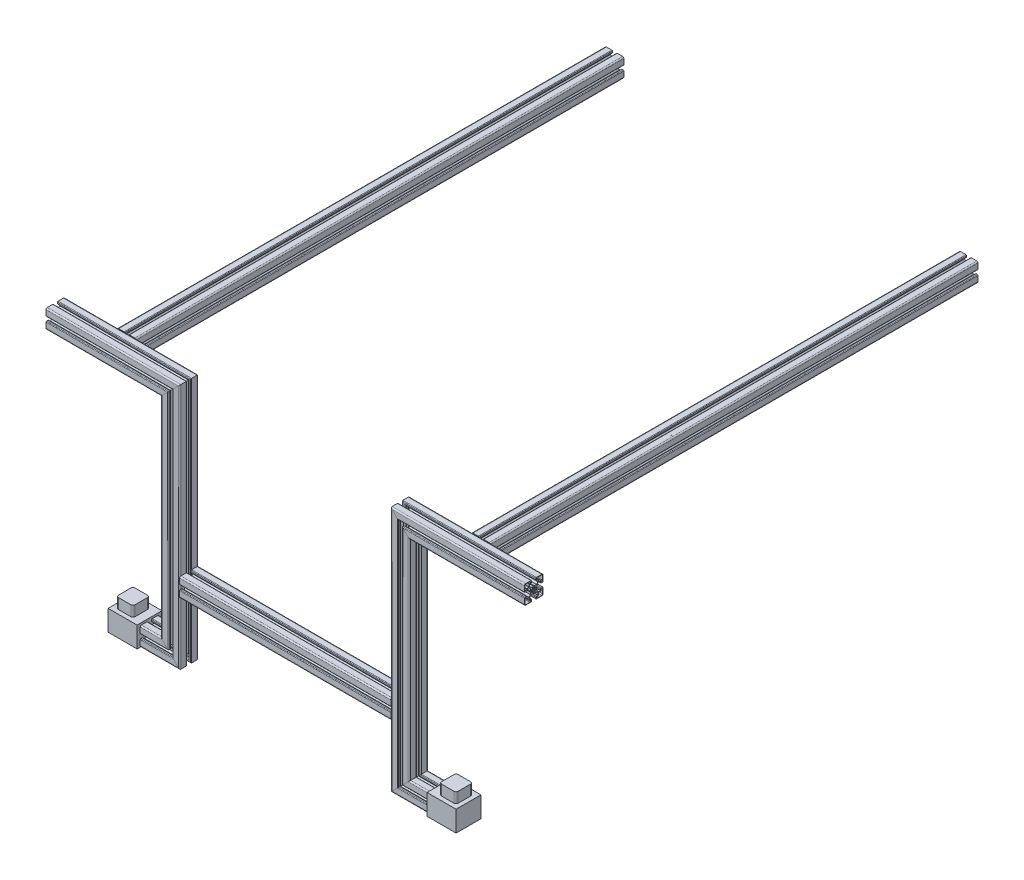
SolidWorks part; units mm, degrees
material "Commercially Pure CP-Ti UNS R50400 (SS)"
ref_plane "Front Plane" through (0, 0, 0) normal (0, 0, 1) x (1, 0, 0)
ref_plane "Top Plane" through (0, 0, 0) normal (0, 1, 0) x (1, 0, 0)
ref_plane "Right Plane" through (0, 0, 0) normal (1, 0, 0) x (0, 0, -1)
sketch "Sketch7" plane through (0, 0, 0) normal (1, 0, 0) x (0, 0, -1)
  line B0 (9.9875, 17.9765) -> (9.5475, 17.9765)
  line B1 (8.0475, 19.4765) -> (8.0475, 19.9765)
  line B2 (9.5475, 21.4765) -> (19.1575, 21.4765)
  line B3 (21.4375, 19.1965) -> (21.4375, 9.5865)
  line B4 (19.9375, 8.0865) -> (19.4375, 8.0865)
  line B5 (17.9375, 9.5865) -> (17.9375, 10.0265)
  line B6 (16.9375, 11.0265) -> (11.3675, 11.0265)
  line B7 (10.9875, 11.4065) -> (10.9875, 16.9765)
  line B8 (17.9765, -9.9875) -> (17.9765, -9.5475)
  line B9 (19.4765, -8.0475) -> (19.9765, -8.0475)
  line B10 (21.4765, -9.5475) -> (21.4765, -19.1575)
  line B11 (19.1965, -21.4375) -> (9.5865, -21.4375)
  line B12 (8.0865, -19.9375) -> (8.0865, -19.4375)
  line B13 (9.5865, -17.9375) -> (10.0265, -17.9375)
  line B14 (11.0265, -16.9375) -> (11.0265, -11.3675)
  line B15 (11.4065, -10.9875) -> (16.9765, -10.9875)
  line B16 (-9.9875, -17.9765) -> (-9.5475, -17.9765)
  line B17 (-8.0475, -19.4765) -> (-8.0475, -19.9765)
  line B18 (-9.5475, -21.4765) -> (-19.1575, -21.4765)
  line B19 (-21.4375, -19.1965) -> (-21.4375, -9.5865)
  line B20 (-19.9375, -8.0865) -> (-19.4375, -8.0865)
  line B21 (-17.9375, -9.5865) -> (-17.9375, -10.0265)
  line B22 (-16.9375, -11.0265) -> (-11.3675, -11.0265)
  line B23 (-10.9875, -11.4065) -> (-10.9875, -16.9765)
  line B24 (-2.1534, -5.7864) -> (-2.5692, -5.6142)
  line B25 (-5.6143, -2.5689) -> (-5.7865, -2.1531)
  line B26 (-5.7864, 2.1534) -> (-5.6142, 2.5692)
  line B27 (-2.5689, 5.6143) -> (-2.1531, 5.7865)
  line B28 (2.1534, 5.7864) -> (2.5692, 5.6142)
  line B29 (5.6143, 2.5689) -> (5.7865, 2.1531)
  line B30 (5.7864, -2.1534) -> (5.6142, -2.5692)
  line B31 (2.5689, -5.6143) -> (2.1531, -5.7865)
  line B32 (-17.9765, 9.9875) -> (-17.9765, 9.5475)
  line B33 (-19.4765, 8.0475) -> (-19.9765, 8.0475)
  line B34 (-21.4765, 9.5475) -> (-21.4765, 19.1575)
  line B35 (-19.1965, 21.4375) -> (-9.5865, 21.4375)
  line B36 (-8.0865, 19.9375) -> (-8.0865, 19.4375)
  line B37 (-9.5865, 17.9375) -> (-10.0265, 17.9375)
  line B38 (-11.0265, 16.9375) -> (-11.0265, 11.3675)
  line B39 (-11.4065, 10.9875) -> (-16.9765, 10.9875)
  line B40 (0.9235, 7.9175) -> (0.0235, 7.4024)
  line B41 (0.0235, 7.4024) -> (-0.8765, 7.9175)
  line B42 (-0.8765, 7.9175) -> (-6.1798, 7.9175)
  line B43 (-6.4485, 8.0288) -> (-9.9152, 11.4955)
  line B44 (-10.0265, 11.7642) -> (-10.0265, 16.0575)
  line B45 (-9.6465, 16.4375) -> (-6.5615, 16.4375)
  line B46 (-5.0415, 17.9575) -> (-5.0415, 20.9175)
  line B47 (-6.5615, 22.4375) -> (-19.4765, 22.4375)
  line B48 (-22.4765, 19.4375) -> (-22.4765, 6.5225)
  line B49 (-20.9565, 5.0025) -> (-17.9965, 5.0025)
  line B50 (-16.4765, 6.5225) -> (-16.4765, 9.6075)
  line B51 (-16.0965, 9.9875) -> (-11.7961, 9.9875)
  line B52 (-11.5274, 9.8762) -> (-8.0678, 6.4166)
  line B53 (-7.9565, 6.1479) -> (-7.9565, 0.8375)
  line B54 (-7.9565, 0.8375) -> (-7.4369, -0.0625)
  line B55 (-7.4369, -0.0625) -> (-7.9565, -0.9625)
  line B56 (-7.9565, -0.9625) -> (-7.9565, -6.2658)
  line B57 (-8.0678, -6.5345) -> (-11.5345, -10.0012)
  line B58 (-11.8032, -10.1125) -> (-16.0965, -10.1125)
  line B59 (-16.4765, -9.7325) -> (-16.4765, -6.6475)
  line B60 (-17.9965, -5.1275) -> (-20.9565, -5.1275)
  line B61 (-22.4765, -6.6475) -> (-22.4765, -19.5625)
  line B62 (-19.4765, -22.5625) -> (-6.5615, -22.5625)
  line B63 (-5.0415, -21.0425) -> (-5.0415, -18.0825)
  line B64 (-6.5615, -16.5625) -> (-9.6465, -16.5625)
  line B65 (-10.0265, -16.1825) -> (-10.0265, -11.8821)
  line B66 (-9.9152, -11.6134) -> (-6.4556, -8.1538)
  line B67 (-6.1869, -8.0425) -> (-0.8765, -8.0425)
  line B68 (-0.8765, -8.0425) -> (0.0235, -7.5274)
  line B69 (0.0235, -7.5274) -> (0.9235, -8.0425)
  line B70 (0.9235, -8.0425) -> (6.2268, -8.0425)
  line B71 (6.4955, -8.1538) -> (9.9622, -11.6205)
  line B72 (10.0735, -11.8892) -> (10.0735, -16.1825)
  line B73 (9.6935, -16.5625) -> (6.6085, -16.5625)
  line B74 (5.0885, -18.0825) -> (5.0885, -21.0425)
  line B75 (6.6085, -22.5625) -> (19.5235, -22.5625)
  line B76 (22.5235, -19.5625) -> (22.5235, -6.6475)
  line B77 (21.0035, -5.1275) -> (18.0435, -5.1275)
  line B78 (16.5235, -6.6475) -> (16.5235, -9.7325)
  line B79 (16.1435, -10.1125) -> (11.8431, -10.1125)
  line B80 (11.5744, -10.0012) -> (8.1148, -6.5416)
  line B81 (8.0035, -6.2729) -> (8.0035, -0.9625)
  line B82 (8.0035, -0.9625) -> (7.4839, -0.0625)
  line B83 (7.4839, -0.0625) -> (8.0035, 0.8375)
  line B84 (8.0035, 0.8375) -> (8.0035, 6.1408)
  line B85 (8.1148, 6.4095) -> (11.5815, 9.8762)
  line B86 (11.8502, 9.9875) -> (16.1435, 9.9875)
  line B87 (16.5235, 9.6075) -> (16.5235, 6.5225)
  line B88 (18.0435, 5.0025) -> (21.0035, 5.0025)
  line B89 (22.5235, 6.5225) -> (22.5235, 19.4375)
  line B90 (19.5235, 22.4375) -> (6.6085, 22.4375)
  line B91 (5.0885, 20.9175) -> (5.0885, 17.9575)
  line B92 (6.6085, 16.4375) -> (9.6935, 16.4375)
  line B93 (10.0735, 16.0575) -> (10.0735, 11.7571)
  line B94 (9.9622, 11.4884) -> (6.5026, 8.0288)
  line B95 (6.2339, 7.9175) -> (0.9235, 7.9175)
  arc B96 (10.9875, 16.9765) -> (9.9875, 17.9765) centre (9.9875, 16.9765) ccw
  arc B97 (8.0475, 19.4765) -> (9.5475, 17.9765) centre (9.5475, 19.4765) ccw
  arc B98 (9.5475, 21.4765) -> (8.0475, 19.9765) centre (9.5475, 19.9765) ccw
  arc B99 (21.4375, 19.1965) -> (19.1575, 21.4765) centre (19.1575, 19.1965) ccw
  arc B100 (19.9375, 8.0865) -> (21.4375, 9.5865) centre (19.9375, 9.5865) ccw
  arc B101 (17.9375, 9.5865) -> (19.4375, 8.0865) centre (19.4375, 9.5865) ccw
  arc B102 (17.9375, 10.0265) -> (16.9375, 11.0265) centre (16.9375, 10.0265) ccw
  arc B103 (10.9875, 11.4065) -> (11.3675, 11.0265) centre (11.3675, 11.4065) ccw
  arc B104 (16.9765, -10.9875) -> (17.9765, -9.9875) centre (16.9765, -9.9875) ccw
  arc B105 (19.4765, -8.0475) -> (17.9765, -9.5475) centre (19.4765, -9.5475) ccw
  arc B106 (21.4765, -9.5475) -> (19.9765, -8.0475) centre (19.9765, -9.5475) ccw
  arc B107 (19.1965, -21.4375) -> (21.4765, -19.1575) centre (19.1965, -19.1575) ccw
  arc B108 (8.0865, -19.9375) -> (9.5865, -21.4375) centre (9.5865, -19.9375) ccw
  arc B109 (9.5865, -17.9375) -> (8.0865, -19.4375) centre (9.5865, -19.4375) ccw
  arc B110 (10.0265, -17.9375) -> (11.0265, -16.9375) centre (10.0265, -16.9375) ccw
  arc B111 (11.4065, -10.9875) -> (11.0265, -11.3675) centre (11.4065, -11.3675) ccw
  arc B112 (-10.9875, -16.9765) -> (-9.9875, -17.9765) centre (-9.9875, -16.9765) ccw
  arc B113 (-8.0475, -19.4765) -> (-9.5475, -17.9765) centre (-9.5475, -19.4765) ccw
  arc B114 (-9.5475, -21.4765) -> (-8.0475, -19.9765) centre (-9.5475, -19.9765) ccw
  arc B115 (-21.4375, -19.1965) -> (-19.1575, -21.4765) centre (-19.1575, -19.1965) ccw
  arc B116 (-19.9375, -8.0865) -> (-21.4375, -9.5865) centre (-19.9375, -9.5865) ccw
  arc B117 (-17.9375, -9.5865) -> (-19.4375, -8.0865) centre (-19.4375, -9.5865) ccw
  arc B118 (-17.9375, -10.0265) -> (-16.9375, -11.0265) centre (-16.9375, -10.0265) ccw
  arc B119 (-10.9875, -11.4065) -> (-11.3675, -11.0265) centre (-11.3675, -11.4065) ccw
  arc B120 (-2.9461, -4.0399) -> (-2.5692, -5.6142) centre (-2.1865, -4.6903) ccw
  arc B121 (-4.0401, -2.9458) -> (-2.9461, -4.0399) centre (0, 0) ccw
  arc B122 (-5.6143, -2.5689) -> (-4.0401, -2.9458) centre (-4.6904, -2.1862) ccw
  arc B123 (-4.9398, -0.7734) -> (-5.7865, -2.1531) centre (-4.8626, -1.7705) ccw
  arc B124 (-4.9398, 0.7737) -> (-4.9398, -0.7734) centre (0, 0) ccw
  arc B125 (-5.7864, 2.1534) -> (-4.9398, 0.7737) centre (-4.8625, 1.7707) ccw
  arc B126 (-4.0399, 2.9461) -> (-5.6142, 2.5692) centre (-4.6903, 2.1865) ccw
  arc B127 (-2.9458, 4.0401) -> (-4.0399, 2.9461) centre (0, 0) ccw
  arc B128 (-2.5689, 5.6143) -> (-2.9458, 4.0401) centre (-2.1862, 4.6904) ccw
  arc B129 (-0.7734, 4.9398) -> (-2.1531, 5.7865) centre (-1.7705, 4.8626) ccw
  arc B130 (0.7737, 4.9398) -> (-0.7734, 4.9398) centre (0, 0) ccw
  arc B131 (2.1534, 5.7864) -> (0.7737, 4.9398) centre (1.7707, 4.8625) ccw
  arc B132 (2.9461, 4.0399) -> (2.5692, 5.6142) centre (2.1865, 4.6903) ccw
  arc B133 (4.0401, 2.9458) -> (2.9461, 4.0399) centre (0, 0) ccw
  arc B134 (5.6143, 2.5689) -> (4.0401, 2.9458) centre (4.6904, 2.1862) ccw
  arc B135 (4.9398, 0.7734) -> (5.7865, 2.1531) centre (4.8626, 1.7705) ccw
  arc B136 (4.9398, -0.7737) -> (4.9398, 0.7734) centre (0, 0) ccw
  arc B137 (5.7864, -2.1534) -> (4.9398, -0.7737) centre (4.8625, -1.7707) ccw
  arc B138 (4.0399, -2.9461) -> (5.6142, -2.5692) centre (4.6903, -2.1865) ccw
  arc B139 (2.9458, -4.0401) -> (4.0399, -2.9461) centre (0, 0) ccw
  arc B140 (2.5689, -5.6143) -> (2.9458, -4.0401) centre (2.1862, -4.6904) ccw
  arc B141 (0.7734, -4.9398) -> (2.1531, -5.7865) centre (1.7705, -4.8626) ccw
  arc B142 (-0.7737, -4.9398) -> (0.7734, -4.9398) centre (0, 0) ccw
  arc B143 (-2.1534, -5.7864) -> (-0.7737, -4.9398) centre (-1.7707, -4.8625) ccw
  arc B144 (-16.9765, 10.9875) -> (-17.9765, 9.9875) centre (-16.9765, 9.9875) ccw
  arc B145 (-19.4765, 8.0475) -> (-17.9765, 9.5475) centre (-19.4765, 9.5475) ccw
  arc B146 (-21.4765, 9.5475) -> (-19.9765, 8.0475) centre (-19.9765, 9.5475) ccw
  arc B147 (-19.1965, 21.4375) -> (-21.4765, 19.1575) centre (-19.1965, 19.1575) ccw
  arc B148 (-8.0865, 19.9375) -> (-9.5865, 21.4375) centre (-9.5865, 19.9375) ccw
  arc B149 (-9.5865, 17.9375) -> (-8.0865, 19.4375) centre (-9.5865, 19.4375) ccw
  arc B150 (-10.0265, 17.9375) -> (-11.0265, 16.9375) centre (-10.0265, 16.9375) ccw
  arc B151 (-11.4065, 10.9875) -> (-11.0265, 11.3675) centre (-11.4065, 11.3675) ccw
  arc B152 (-6.4485, 8.0288) -> (-6.1798, 7.9175) centre (-6.1798, 8.2975) ccw
  arc B153 (-10.0265, 11.7642) -> (-9.9152, 11.4955) centre (-9.6465, 11.7642) ccw
  arc B154 (-9.6465, 16.4375) -> (-10.0265, 16.0575) centre (-9.6465, 16.0575) ccw
  arc B155 (-6.5615, 16.4375) -> (-5.0415, 17.9575) centre (-6.5615, 17.9575) ccw
  arc B156 (-5.0415, 20.9175) -> (-6.5615, 22.4375) centre (-6.5615, 20.9175) ccw
  arc B157 (-19.4765, 22.4375) -> (-22.4765, 19.4375) centre (-19.4765, 19.4375) ccw
  arc B158 (-22.4765, 6.5225) -> (-20.9565, 5.0025) centre (-20.9565, 6.5225) ccw
  arc B159 (-17.9965, 5.0025) -> (-16.4765, 6.5225) centre (-17.9965, 6.5225) ccw
  arc B160 (-16.0965, 9.9875) -> (-16.4765, 9.6075) centre (-16.0965, 9.6075) ccw
  arc B161 (-11.5274, 9.8762) -> (-11.7961, 9.9875) centre (-11.7961, 9.6075) ccw
  arc B162 (-7.9565, 6.1479) -> (-8.0678, 6.4166) centre (-8.3365, 6.1479) ccw
  arc B163 (-8.0678, -6.5345) -> (-7.9565, -6.2658) centre (-8.3365, -6.2658) ccw
  arc B164 (-11.8032, -10.1125) -> (-11.5345, -10.0012) centre (-11.8032, -9.7325) ccw
  arc B165 (-16.4765, -9.7325) -> (-16.0965, -10.1125) centre (-16.0965, -9.7325) ccw
  arc B166 (-16.4765, -6.6475) -> (-17.9965, -5.1275) centre (-17.9965, -6.6475) ccw
  arc B167 (-20.9565, -5.1275) -> (-22.4765, -6.6475) centre (-20.9565, -6.6475) ccw
  arc B168 (-22.4765, -19.5625) -> (-19.4765, -22.5625) centre (-19.4765, -19.5625) ccw
  arc B169 (-6.5615, -22.5625) -> (-5.0415, -21.0425) centre (-6.5615, -21.0425) ccw
  arc B170 (-5.0415, -18.0825) -> (-6.5615, -16.5625) centre (-6.5615, -18.0825) ccw
  arc B171 (-10.0265, -16.1825) -> (-9.6465, -16.5625) centre (-9.6465, -16.1825) ccw
  arc B172 (-9.9152, -11.6134) -> (-10.0265, -11.8821) centre (-9.6465, -11.8821) ccw
  arc B173 (-6.1869, -8.0425) -> (-6.4556, -8.1538) centre (-6.1869, -8.4225) ccw
  arc B174 (6.4955, -8.1538) -> (6.2268, -8.0425) centre (6.2268, -8.4225) ccw
  arc B175 (10.0735, -11.8892) -> (9.9622, -11.6205) centre (9.6935, -11.8892) ccw
  arc B176 (9.6935, -16.5625) -> (10.0735, -16.1825) centre (9.6935, -16.1825) ccw
  arc B177 (6.6085, -16.5625) -> (5.0885, -18.0825) centre (6.6085, -18.0825) ccw
  arc B178 (5.0885, -21.0425) -> (6.6085, -22.5625) centre (6.6085, -21.0425) ccw
  arc B179 (19.5235, -22.5625) -> (22.5235, -19.5625) centre (19.5235, -19.5625) ccw
  arc B180 (22.5235, -6.6475) -> (21.0035, -5.1275) centre (21.0035, -6.6475) ccw
  arc B181 (18.0435, -5.1275) -> (16.5235, -6.6475) centre (18.0435, -6.6475) ccw
  arc B182 (16.1435, -10.1125) -> (16.5235, -9.7325) centre (16.1435, -9.7325) ccw
  arc B183 (11.5744, -10.0012) -> (11.8431, -10.1125) centre (11.8431, -9.7325) ccw
  arc B184 (8.0035, -6.2729) -> (8.1148, -6.5416) centre (8.3835, -6.2729) ccw
  arc B185 (8.1148, 6.4095) -> (8.0035, 6.1408) centre (8.3835, 6.1408) ccw
  arc B186 (11.8502, 9.9875) -> (11.5815, 9.8762) centre (11.8502, 9.6075) ccw
  arc B187 (16.5235, 9.6075) -> (16.1435, 9.9875) centre (16.1435, 9.6075) ccw
  arc B188 (16.5235, 6.5225) -> (18.0435, 5.0025) centre (18.0435, 6.5225) ccw
  arc B189 (21.0035, 5.0025) -> (22.5235, 6.5225) centre (21.0035, 6.5225) ccw
  arc B190 (22.5235, 19.4375) -> (19.5235, 22.4375) centre (19.5235, 19.4375) ccw
  arc B191 (6.6085, 22.4375) -> (5.0885, 20.9175) centre (6.6085, 20.9175) ccw
  arc B192 (5.0885, 17.9575) -> (6.6085, 16.4375) centre (6.6085, 17.9575) ccw
  arc B193 (10.0735, 16.0575) -> (9.6935, 16.4375) centre (9.6935, 16.0575) ccw
  arc B194 (9.9622, 11.4884) -> (10.0735, 11.7571) centre (9.6935, 11.7571) ccw
  arc B195 (6.2339, 7.9175) -> (6.5026, 8.0288) centre (6.2339, 8.2975) ccw
sketch_block_instance "Block1-1"
sketch_block "Block1"
sketch "Sketch1" [suppressed] plane through (0, 0, 0) normal (0, 0, 1) x (1, 0, 0)
  line L0 (0, 0) -> (125, 0)
  line L1 (125, 0) -> (125, 150)
  line L2 (125, 150) -> (337, 150)
  dimension "D1" = 337
  dimension "D2" = 125
  dimension "D3" = 150
sketch "Sketch2" [suppressed] plane through (0, 0, 0) normal (1, 0, 0) x (0, 0, -1)
  line L0 (-33.5, -41) -> (-31.5, -41)
  line L1 (-31.5, -43) -> (-42, -43)
  line L2 (-43, -42) -> (-43, -31.5)
  line L3 (-41, -31.5) -> (-41, -33.5)
  line L4 (-40, -34.5) -> (-34.88, -34.5)
  line L5 (-34.5, -34.88) -> (-34.5, -40)
  line L6 (-16.657, -26.2238) -> (-18.284, -25.188)
  line L7 (-19.8123, -26.7162) -> (-18.7764, -28.3429)
  line L8 (-21.0015, -29.2647) -> (-21.4195, -27.3819)
  line L9 (-23.5808, -27.3818) -> (-23.9986, -29.2645)
  line L10 (-26.2238, -28.343) -> (-25.188, -26.716)
  line L11 (-26.7162, -25.1877) -> (-28.3429, -26.2236)
  line L12 (-29.2647, -23.9985) -> (-27.3819, -23.5805)
  line L13 (-27.3818, -21.4192) -> (-29.2645, -21.0014)
  line L14 (-28.343, -18.7762) -> (-26.716, -19.812)
  line L15 (-25.1877, -18.2838) -> (-26.2236, -16.6571)
  line L16 (-23.9985, -15.7353) -> (-23.5805, -17.6181)
  line L17 (-21.4192, -17.6182) -> (-21.0014, -15.7355)
  line L18 (-18.7762, -16.657) -> (-19.812, -18.284)
  line L19 (-18.2838, -19.8123) -> (-16.6571, -18.7764)
  line L20 (-15.7353, -21.0015) -> (-17.6181, -21.4195)
  line L21 (-17.6182, -23.5808) -> (-15.7355, -23.9986)
  line L22 (41, -33.5) -> (41, -31.5)
  line L23 (43, -31.5) -> (43, -42)
  line L24 (42, -43) -> (31.5, -43)
  line L25 (31.5, -41) -> (33.5, -41)
  line L26 (34.5, -40) -> (34.5, -34.88)
  line L27 (34.88, -34.5) -> (40, -34.5)
  line L28 (26.7162, -19.8123) -> (28.3429, -18.7764)
  line L29 (29.2647, -21.0015) -> (27.3819, -21.4195)
  line L30 (27.3818, -23.5808) -> (29.2645, -23.9986)
  line L31 (28.343, -26.2238) -> (26.716, -25.188)
  line L32 (25.1877, -26.7162) -> (26.2236, -28.3429)
  line L33 (23.9985, -29.2647) -> (23.5805, -27.3819)
  line L34 (21.4192, -27.3818) -> (21.0014, -29.2645)
  line L35 (18.7762, -28.343) -> (19.812, -26.716)
  line L36 (18.2838, -25.1877) -> (16.6571, -26.2236)
  line L37 (15.7353, -23.9985) -> (17.6181, -23.5805)
  line L38 (17.6182, -21.4192) -> (15.7355, -21.0014)
  line L39 (16.657, -18.7762) -> (18.284, -19.812)
  line L40 (19.8123, -18.2838) -> (18.7764, -16.6571)
  line L41 (21.0015, -15.7353) -> (21.4195, -17.6181)
  line L42 (23.5808, -17.6182) -> (23.9986, -15.7355)
  line L43 (26.2238, -16.657) -> (25.188, -18.284)
  line L44 (34.5, 34.88) -> (34.5, 40)
  line L45 (33.5, 41) -> (31.5, 41)
  line L46 (31.5, 43) -> (42, 43)
  line L47 (43, 42) -> (43, 31.5)
  line L48 (41, 31.5) -> (41, 33.5)
  line L49 (40, 34.5) -> (34.88, 34.5)
  line L50 (26.7162, 25.1877) -> (28.3429, 26.2236)
  line L51 (29.2647, 23.9985) -> (27.3819, 23.5805)
  line L52 (27.3818, 21.4192) -> (29.2645, 21.0014)
  line L53 (28.343, 18.7762) -> (26.716, 19.812)
  line L54 (25.1877, 18.2838) -> (26.2236, 16.6571)
  line L55 (23.9985, 15.7353) -> (23.5805, 17.6181)
  line L56 (21.4192, 17.6182) -> (21.0014, 15.7355)
  line L57 (18.7762, 16.657) -> (19.812, 18.284)
  line L58 (18.2838, 19.8123) -> (16.6571, 18.7764)
  line L59 (15.7353, 21.0015) -> (17.6181, 21.4195)
  line L60 (17.6182, 23.5808) -> (15.7355, 23.9986)
  line L61 (16.657, 26.2238) -> (18.284, 25.188)
  line L62 (19.8123, 26.7162) -> (18.7764, 28.3429)
  line L63 (21.0015, 29.2647) -> (21.4195, 27.3819)
  line L64 (23.5808, 27.3818) -> (23.9986, 29.2645)
  line L65 (26.2238, 28.343) -> (25.188, 26.716)
  line L66 (-41, 33.5) -> (-41, 31.5)
  line L67 (-43, 31.5) -> (-43, 42)
  line L68 (-42, 43) -> (-31.5, 43)
  line L69 (-31.5, 41) -> (-33.5, 41)
  line L70 (-34.5, 40) -> (-34.5, 34.88)
  line L71 (-34.88, 34.5) -> (-40, 34.5)
  line L72 (-16.657, 18.7762) -> (-18.284, 19.812)
  line L73 (-19.8123, 18.2838) -> (-18.7764, 16.6571)
  line L74 (-21.0015, 15.7353) -> (-21.4195, 17.6181)
  line L75 (-23.5808, 17.6182) -> (-23.9986, 15.7355)
  line L76 (-26.2238, 16.657) -> (-25.188, 18.284)
  line L77 (-26.7162, 19.8123) -> (-28.3429, 18.7764)
  line L78 (-29.2647, 21.0015) -> (-27.3819, 21.4195)
  line L79 (-27.3818, 23.5808) -> (-29.2645, 23.9986)
  line L80 (-28.343, 26.2238) -> (-26.716, 25.188)
  line L81 (-25.1877, 26.7162) -> (-26.2236, 28.3429)
  line L82 (-23.9985, 29.2647) -> (-23.5805, 27.3819)
  line L83 (-21.4192, 27.3818) -> (-21.0014, 29.2645)
  line L84 (-18.7762, 28.343) -> (-19.812, 26.716)
  line L85 (-18.2838, 25.1877) -> (-16.6571, 26.2236)
  line L86 (-15.7353, 23.9985) -> (-17.6181, 23.5805)
  line L87 (-17.6182, 21.4192) -> (-15.7355, 21.0014)
  line L88 (39, -10.16) -> (33.3774, -10.16)
  line L89 (31.9632, -10.7458) -> (29.8203, -12.8887)
  line L90 (29.5516, -13) -> (23.4, -13)
  line L91 (23.4, -13) -> (22.5, -13.5151)
  line L92 (22.5, -13.5151) -> (21.6, -13)
  line L93 (21.6, -13) -> (15, -13)
  line L94 (13, -15) -> (13, -21.6)
  line L95 (13, -21.6) -> (13.5196, -22.5)
  line L96 (13.5196, -22.5) -> (13, -23.4)
  line L97 (13, -23.4) -> (13, -29.5516)
  line L98 (12.8887, -29.8203) -> (11.3787, -31.3303)
  line L99 (10.5, -33.4516) -> (10.5, -40)
  line L100 (11.5, -41) -> (13.5, -41)
  line L101 (13.5, -43) -> (-13.5, -43)
  line L102 (-13.5, -41) -> (-11.5, -41)
  line L103 (-10.5, -40) -> (-10.5, -33.4516)
  line L104 (-11.3787, -31.3303) -> (-12.8887, -29.8203)
  line L105 (-13, -29.5516) -> (-13, -23.4)
  line L106 (-13, -23.4) -> (-13.5196, -22.5)
  line L107 (-13.5196, -22.5) -> (-13, -21.6)
  line L108 (-13, -21.6) -> (-13, -15)
  line L109 (-15, -13) -> (-21.6, -13)
  line L110 (-21.6, -13) -> (-22.5, -13.5151)
  line L111 (-22.5, -13.5151) -> (-23.4, -13)
  line L112 (-23.4, -13) -> (-29.5516, -13)
  line L113 (-29.8203, -12.8887) -> (-31.9632, -10.7458)
  line L114 (-33.3774, -10.16) -> (-39, -10.16)
  line L115 (-41, -12.16) -> (-41, -13.5)
  line L116 (-43, -13.5) -> (-43, 13.5)
  line L117 (-41, 13.5) -> (-41, 12.16)
  line L118 (-39, 10.16) -> (-33.3774, 10.16)
  line L119 (-31.9632, 10.7458) -> (-29.8203, 12.8887)
  line L120 (-29.5516, 13) -> (-23.4, 13)
  line L121 (-23.4, 13) -> (-22.5, 13.5151)
  line L122 (-22.5, 13.5151) -> (-21.6, 13)
  line L123 (-21.6, 13) -> (-15, 13)
  line L124 (-13, 15) -> (-13, 21.6)
  line L125 (-13, 21.6) -> (-13.5196, 22.5)
  line L126 (-13.5196, 22.5) -> (-13, 23.4)
  line L127 (-13, 23.4) -> (-13, 29.5516)
  line L128 (-12.8887, 29.8203) -> (-11.3787, 31.3303)
  line L129 (-10.5, 33.4516) -> (-10.5, 40)
  line L130 (-11.5, 41) -> (-13.5, 41)
  line L131 (-13.5, 43) -> (13.5, 43)
  line L132 (13.5, 41) -> (11.5, 41)
  line L133 (10.5, 40) -> (10.5, 33.4516)
  line L134 (11.3787, 31.3303) -> (12.8887, 29.8203)
  line L135 (13, 29.5516) -> (13, 23.4)
  line L136 (13, 23.4) -> (13.5196, 22.5)
  line L137 (13.5196, 22.5) -> (13, 21.6)
  line L138 (13, 21.6) -> (13, 15)
  line L139 (15, 13) -> (21.6, 13)
  line L140 (21.6, 13) -> (22.5, 13.5151)
  line L141 (22.5, 13.5151) -> (23.4, 13)
  line L142 (23.4, 13) -> (29.5516, 13)
  line L143 (29.8203, 12.8887) -> (31.9581, 10.7509)
  line L144 (33.3723, 10.1651) -> (39, 10.1651)
  line L145 (41, 12.1651) -> (41, 13.5)
  line L146 (43, 13.5) -> (43, -13.5)
  line L147 (41, -13.5) -> (41, -12.16)
  line L148 (45, -15.915) -> (45, 15.915)
  line L149 (43.48, 17.435) -> (40.52, 17.435)
  line L150 (39, 15.915) -> (39, 13.45)
  line L151 (38, 12.45) -> (34.9984, 12.45)
  line L152 (34.7297, 12.5613) -> (32.1113, 15.1797)
  line L153 (32, 15.4484) -> (32, 21.6)
  line L154 (32, 21.6) -> (31.4804, 22.5)
  line L155 (31.4804, 22.5) -> (32, 23.4)
  line L156 (32, 23.4) -> (32, 29.5516)
  line L157 (32.1113, 29.8203) -> (34.7297, 32.4387)
  line L158 (34.9984, 32.55) -> (38, 32.55)
  line L159 (39, 31.55) -> (39, 29.085)
  line L160 (40.52, 27.565) -> (43.48, 27.565)
  line L161 (45, 29.085) -> (45, 42)
  line L162 (42, 45) -> (29.085, 45)
  line L163 (27.565, 43.48) -> (27.565, 40.52)
  line L164 (29.085, 39) -> (31.55, 39)
  line L165 (32.55, 38) -> (32.55, 34.9984)
  line L166 (32.4387, 34.7297) -> (29.8203, 32.1113)
  line L167 (29.5516, 32) -> (23.4, 32)
  line L168 (23.4, 32) -> (22.5, 31.4849)
  line L169 (22.5, 31.4849) -> (21.6, 32)
  line L170 (21.6, 32) -> (15.4484, 32)
  line L171 (15.1797, 32.1113) -> (12.5613, 34.7297)
  line L172 (12.45, 34.9984) -> (12.45, 38)
  line L173 (13.45, 39) -> (15.915, 39)
  line L174 (17.435, 40.52) -> (17.435, 43.48)
  line L175 (15.915, 45) -> (-15.915, 45)
  line L176 (-17.435, 43.48) -> (-17.435, 40.52)
  line L177 (-15.915, 39) -> (-13.45, 39)
  line L178 (-12.45, 38) -> (-12.45, 34.9984)
  line L179 (-12.5613, 34.7297) -> (-15.1797, 32.1113)
  line L180 (-15.4484, 32) -> (-21.6, 32)
  line L181 (-21.6, 32) -> (-22.5, 31.4849)
  line L182 (-22.5, 31.4849) -> (-23.4, 32)
  line L183 (-23.4, 32) -> (-29.5516, 32)
  line L184 (-29.8203, 32.1113) -> (-32.4387, 34.7297)
  line L185 (-32.55, 34.9984) -> (-32.55, 38)
  line L186 (-31.55, 39) -> (-29.085, 39)
  line L187 (-27.565, 40.52) -> (-27.565, 43.48)
  line L188 (-29.085, 45) -> (-42, 45)
  line L189 (-45, 42) -> (-45, 29.085)
  line L190 (-43.48, 27.565) -> (-40.52, 27.565)
  line L191 (-39, 29.085) -> (-39, 31.55)
  line L192 (-38, 32.55) -> (-34.9984, 32.55)
  line L193 (-34.7297, 32.4387) -> (-32.1113, 29.8203)
  line L194 (-32, 29.5516) -> (-32, 23.4)
  line L195 (-32, 23.4) -> (-31.4804, 22.5)
  line L196 (-31.4804, 22.5) -> (-32, 21.6)
  line L197 (-32, 21.6) -> (-32, 15.4484)
  line L198 (-32.1113, 15.1797) -> (-34.7297, 12.5613)
  line L199 (-34.9984, 12.45) -> (-38, 12.45)
  line L200 (-39, 13.45) -> (-39, 15.915)
  line L201 (-40.52, 17.435) -> (-43.48, 17.435)
  line L202 (-45, 15.915) -> (-45, -15.915)
  line L203 (-43.48, -17.435) -> (-40.52, -17.435)
  line L204 (-39, -15.915) -> (-39, -13.45)
  line L205 (-38, -12.45) -> (-34.9984, -12.45)
  line L206 (-34.7297, -12.5613) -> (-32.1113, -15.1797)
  line L207 (-32, -15.4484) -> (-32, -21.6)
  line L208 (-32, -21.6) -> (-31.4804, -22.5)
  line L209 (-31.4804, -22.5) -> (-32, -23.4)
  line L210 (-32, -23.4) -> (-32, -29.5516)
  line L211 (-32.1113, -29.8203) -> (-34.7297, -32.4387)
  line L212 (-34.9984, -32.55) -> (-38, -32.55)
  line L213 (-39, -31.55) -> (-39, -29.085)
  line L214 (-40.52, -27.565) -> (-43.48, -27.565)
  line L215 (-45, -29.085) -> (-45, -42)
  line L216 (-42, -45) -> (-29.085, -45)
  line L217 (-27.565, -43.48) -> (-27.565, -40.52)
  line L218 (-29.085, -39) -> (-31.55, -39)
  line L219 (-32.55, -38) -> (-32.55, -34.9984)
  line L220 (-32.4387, -34.7297) -> (-29.8203, -32.1113)
  line L221 (-29.5516, -32) -> (-23.4, -32)
  line L222 (-23.4, -32) -> (-22.5, -31.4849)
  line L223 (-22.5, -31.4849) -> (-21.6, -32)
  line L224 (-21.6, -32) -> (-15.4484, -32)
  line L225 (-15.1797, -32.1113) -> (-12.5613, -34.7297)
  line L226 (-12.45, -34.9984) -> (-12.45, -38)
  line L227 (-13.45, -39) -> (-15.915, -39)
  line L228 (-17.435, -40.52) -> (-17.435, -43.48)
  line L229 (-15.915, -45) -> (15.915, -45)
  line L230 (17.435, -43.48) -> (17.435, -40.52)
  line L231 (15.915, -39) -> (13.45, -39)
  line L232 (12.45, -38) -> (12.45, -34.9984)
  line L233 (12.5613, -34.7297) -> (15.1797, -32.1113)
  line L234 (15.4484, -32) -> (21.6, -32)
  line L235 (21.6, -32) -> (22.5, -31.4849)
  line L236 (22.5, -31.4849) -> (23.4, -32)
  line L237 (23.4, -32) -> (29.5516, -32)
  line L238 (29.8203, -32.1113) -> (32.4387, -34.7297)
  line L239 (32.55, -34.9984) -> (32.55, -38)
  line L240 (31.55, -39) -> (29.085, -39)
  line L241 (27.565, -40.52) -> (27.565, -43.48)
  line L242 (29.085, -45) -> (42, -45)
  line L243 (45, -42) -> (45, -29.085)
  line L244 (43.48, -27.565) -> (40.52, -27.565)
  line L245 (39, -29.085) -> (39, -31.55)
  line L246 (38, -32.55) -> (34.9984, -32.55)
  line L247 (34.7297, -32.4387) -> (32.1113, -29.8203)
  line L248 (32, -29.5516) -> (32, -23.4)
  line L249 (32, -23.4) -> (31.4804, -22.5)
  line L250 (31.4804, -22.5) -> (32, -21.6)
  line L251 (32, -21.6) -> (32, -15.4484)
  line L252 (32.1113, -15.1797) -> (34.7297, -12.5613)
  line L253 (34.9984, -12.45) -> (38, -12.45)
  line L254 (39, -13.45) -> (39, -15.915)
  line L255 (40.52, -17.435) -> (43.48, -17.435)
  arc A0 (-34.5, -40) -> (-33.5, -41) centre (-33.5, -40) ccw
  arc A1 (-31.5, -43) -> (-31.5, -41) centre (-31.5, -42) ccw
  arc A2 (-43, -42) -> (-42, -43) centre (-42, -42) ccw
  arc A3 (-41, -31.5) -> (-43, -31.5) centre (-42, -31.5) ccw
  arc A4 (-41, -33.5) -> (-40, -34.5) centre (-40, -33.5) ccw
  arc A5 (-34.5, -34.88) -> (-34.88, -34.5) centre (-34.88, -34.88) ccw
  arc A6 (-15.2086, -25.7917) -> (-15.0167, -25.3284) centre (-22.5, -22.5) ccw
  arc A7 (-16.657, -26.2238) -> (-15.2086, -25.7917) centre (-16.12, -25.3802) ccw
  arc A8 (-19.8123, -26.7162) -> (-18.284, -25.188) centre (-22.5, -22.5) ccw
  arc A9 (-19.2085, -29.7915) -> (-18.7764, -28.3429) centre (-19.6199, -28.8801) ccw
  arc A10 (-19.6717, -29.9834) -> (-19.2085, -29.7915) centre (-22.5, -22.5) ccw
  arc A11 (-21.0015, -29.2647) -> (-19.6717, -29.9834) centre (-20.0253, -29.048) ccw
  arc A12 (-23.5808, -27.3818) -> (-21.4195, -27.3819) centre (-22.5, -22.5) ccw
  arc A13 (-25.3284, -29.9833) -> (-23.9986, -29.2645) centre (-24.9749, -29.0479) ccw
  arc A14 (-25.7917, -29.7914) -> (-25.3284, -29.9833) centre (-22.5, -22.5) ccw
  arc A15 (-26.2238, -28.343) -> (-25.7917, -29.7914) centre (-25.3802, -28.88) ccw
  arc A16 (-26.7162, -25.1877) -> (-25.188, -26.716) centre (-22.5, -22.5) ccw
  arc A17 (-29.7915, -25.7915) -> (-28.3429, -26.2236) centre (-28.8801, -25.3801) ccw
  arc A18 (-29.9834, -25.3283) -> (-29.7915, -25.7915) centre (-22.5, -22.5) ccw
  arc A19 (-29.2647, -23.9985) -> (-29.9834, -25.3283) centre (-29.048, -24.9747) ccw
  arc A20 (-27.3818, -21.4192) -> (-27.3819, -23.5805) centre (-22.5, -22.5) ccw
  arc A21 (-29.9833, -19.6716) -> (-29.2645, -21.0014) centre (-29.0479, -20.0251) ccw
  arc A22 (-29.7914, -19.2083) -> (-29.9833, -19.6716) centre (-22.5, -22.5) ccw
  arc A23 (-28.343, -18.7762) -> (-29.7914, -19.2083) centre (-28.88, -19.6198) ccw
  arc A24 (-25.1877, -18.2838) -> (-26.716, -19.812) centre (-22.5, -22.5) ccw
  arc A25 (-25.7915, -15.2085) -> (-26.2236, -16.6571) centre (-25.3801, -16.1199) ccw
  arc A26 (-25.3283, -15.0166) -> (-25.7915, -15.2085) centre (-22.5, -22.5) ccw
  arc A27 (-23.9985, -15.7353) -> (-25.3283, -15.0166) centre (-24.9747, -15.952) ccw
  arc A28 (-21.4192, -17.6182) -> (-23.5805, -17.6181) centre (-22.5, -22.5) ccw
  arc A29 (-19.6716, -15.0167) -> (-21.0014, -15.7355) centre (-20.0251, -15.9521) ccw
  arc A30 (-19.2083, -15.2086) -> (-19.6716, -15.0167) centre (-22.5, -22.5) ccw
  arc A31 (-18.7762, -16.657) -> (-19.2083, -15.2086) centre (-19.6198, -16.12) ccw
  arc A32 (-18.2838, -19.8123) -> (-19.812, -18.284) centre (-22.5, -22.5) ccw
  arc A33 (-15.2085, -19.2085) -> (-16.6571, -18.7764) centre (-16.1199, -19.6199) ccw
  arc A34 (-15.0166, -19.6717) -> (-15.2085, -19.2085) centre (-22.5, -22.5) ccw
  arc A35 (-15.7353, -21.0015) -> (-15.0166, -19.6717) centre (-15.952, -20.0253) ccw
  arc A36 (-17.6182, -23.5808) -> (-17.6181, -21.4195) centre (-22.5, -22.5) ccw
  arc A37 (-15.0167, -25.3284) -> (-15.7355, -23.9986) centre (-15.9521, -24.9749) ccw
  arc A38 (40, -34.5) -> (41, -33.5) centre (40, -33.5) ccw
  arc A39 (43, -31.5) -> (41, -31.5) centre (42, -31.5) ccw
  arc A40 (42, -43) -> (43, -42) centre (42, -42) ccw
  arc A41 (31.5, -41) -> (31.5, -43) centre (31.5, -42) ccw
  arc A42 (33.5, -41) -> (34.5, -40) centre (33.5, -40) ccw
  arc A43 (34.88, -34.5) -> (34.5, -34.88) centre (34.88, -34.88) ccw
  arc A44 (26.7162, -19.8123) -> (25.188, -18.284) centre (22.5, -22.5) ccw
  arc A45 (29.7915, -19.2085) -> (28.3429, -18.7764) centre (28.8801, -19.6199) ccw
  arc A46 (29.9834, -19.6717) -> (29.7915, -19.2085) centre (22.5, -22.5) ccw
  arc A47 (29.2647, -21.0015) -> (29.9834, -19.6717) centre (29.048, -20.0253) ccw
  arc A48 (27.3818, -23.5808) -> (27.3819, -21.4195) centre (22.5, -22.5) ccw
  arc A49 (29.9833, -25.3284) -> (29.2645, -23.9986) centre (29.0479, -24.9749) ccw
  arc A50 (29.7914, -25.7917) -> (29.9833, -25.3284) centre (22.5, -22.5) ccw
  arc A51 (28.343, -26.2238) -> (29.7914, -25.7917) centre (28.88, -25.3802) ccw
  arc A52 (25.1877, -26.7162) -> (26.716, -25.188) centre (22.5, -22.5) ccw
  arc A53 (25.7915, -29.7915) -> (26.2236, -28.3429) centre (25.3801, -28.8801) ccw
  arc A54 (25.3283, -29.9834) -> (25.7915, -29.7915) centre (22.5, -22.5) ccw
  arc A55 (23.9985, -29.2647) -> (25.3283, -29.9834) centre (24.9747, -29.048) ccw
  arc A56 (21.4192, -27.3818) -> (23.5805, -27.3819) centre (22.5, -22.5) ccw
  arc A57 (19.6716, -29.9833) -> (21.0014, -29.2645) centre (20.0251, -29.0479) ccw
  arc A58 (19.2083, -29.7914) -> (19.6716, -29.9833) centre (22.5, -22.5) ccw
  arc A59 (18.7762, -28.343) -> (19.2083, -29.7914) centre (19.6198, -28.88) ccw
  arc A60 (18.2838, -25.1877) -> (19.812, -26.716) centre (22.5, -22.5) ccw
  arc A61 (15.2085, -25.7915) -> (16.6571, -26.2236) centre (16.1199, -25.3801) ccw
  arc A62 (15.0166, -25.3283) -> (15.2085, -25.7915) centre (22.5, -22.5) ccw
  arc A63 (15.7353, -23.9985) -> (15.0166, -25.3283) centre (15.952, -24.9747) ccw
  arc A64 (17.6182, -21.4192) -> (17.6181, -23.5805) centre (22.5, -22.5) ccw
  arc A65 (15.0167, -19.6716) -> (15.7355, -21.0014) centre (15.9521, -20.0251) ccw
  arc A66 (15.2086, -19.2083) -> (15.0167, -19.6716) centre (22.5, -22.5) ccw
  arc A67 (16.657, -18.7762) -> (15.2086, -19.2083) centre (16.12, -19.6198) ccw
  arc A68 (19.8123, -18.2838) -> (18.284, -19.812) centre (22.5, -22.5) ccw
  arc A69 (19.2085, -15.2085) -> (18.7764, -16.6571) centre (19.6199, -16.1199) ccw
  arc A70 (19.6717, -15.0166) -> (19.2085, -15.2085) centre (22.5, -22.5) ccw
  arc A71 (21.0015, -15.7353) -> (19.6717, -15.0166) centre (20.0253, -15.952) ccw
  arc A72 (23.5808, -17.6182) -> (21.4195, -17.6181) centre (22.5, -22.5) ccw
  arc A73 (25.3284, -15.0167) -> (23.9986, -15.7355) centre (24.9749, -15.9521) ccw
  arc A74 (25.7917, -15.2086) -> (25.3284, -15.0167) centre (22.5, -22.5) ccw
  arc A75 (26.2238, -16.657) -> (25.7917, -15.2086) centre (25.3802, -16.12) ccw
  arc A76 (34.5, 34.88) -> (34.88, 34.5) centre (34.88, 34.88) ccw
  arc A77 (34.5, 40) -> (33.5, 41) centre (33.5, 40) ccw
  arc A78 (31.5, 43) -> (31.5, 41) centre (31.5, 42) ccw
  arc A79 (43, 42) -> (42, 43) centre (42, 42) ccw
  arc A80 (41, 31.5) -> (43, 31.5) centre (42, 31.5) ccw
  arc A81 (41, 33.5) -> (40, 34.5) centre (40, 33.5) ccw
  arc A82 (26.7162, 25.1877) -> (25.188, 26.716) centre (22.5, 22.5) ccw
  arc A83 (29.7915, 25.7915) -> (28.3429, 26.2236) centre (28.8801, 25.3801) ccw
  arc A84 (29.9834, 25.3283) -> (29.7915, 25.7915) centre (22.5, 22.5) ccw
  arc A85 (29.2647, 23.9985) -> (29.9834, 25.3283) centre (29.048, 24.9747) ccw
  arc A86 (27.3818, 21.4192) -> (27.3819, 23.5805) centre (22.5, 22.5) ccw
  arc A87 (29.9833, 19.6716) -> (29.2645, 21.0014) centre (29.0479, 20.0251) ccw
  arc A88 (29.7914, 19.2083) -> (29.9833, 19.6716) centre (22.5, 22.5) ccw
  arc A89 (28.343, 18.7762) -> (29.7914, 19.2083) centre (28.88, 19.6198) ccw
  arc A90 (25.1877, 18.2838) -> (26.716, 19.812) centre (22.5, 22.5) ccw
  arc A91 (25.7915, 15.2085) -> (26.2236, 16.6571) centre (25.3801, 16.1199) ccw
  arc A92 (25.3283, 15.0166) -> (25.7915, 15.2085) centre (22.5, 22.5) ccw
  arc A93 (23.9985, 15.7353) -> (25.3283, 15.0166) centre (24.9747, 15.952) ccw
  arc A94 (21.4192, 17.6182) -> (23.5805, 17.6181) centre (22.5, 22.5) ccw
  arc A95 (19.6716, 15.0167) -> (21.0014, 15.7355) centre (20.0251, 15.9521) ccw
  arc A96 (19.2083, 15.2086) -> (19.6716, 15.0167) centre (22.5, 22.5) ccw
  arc A97 (18.7762, 16.657) -> (19.2083, 15.2086) centre (19.6198, 16.12) ccw
  arc A98 (18.2838, 19.8123) -> (19.812, 18.284) centre (22.5, 22.5) ccw
  arc A99 (15.2085, 19.2085) -> (16.6571, 18.7764) centre (16.1199, 19.6199) ccw
  arc A100 (15.0166, 19.6717) -> (15.2085, 19.2085) centre (22.5, 22.5) ccw
  arc A101 (15.7353, 21.0015) -> (15.0166, 19.6717) centre (15.952, 20.0253) ccw
  arc A102 (17.6182, 23.5808) -> (17.6181, 21.4195) centre (22.5, 22.5) ccw
  arc A103 (15.0167, 25.3284) -> (15.7355, 23.9986) centre (15.9521, 24.9749) ccw
  arc A104 (15.2086, 25.7917) -> (15.0167, 25.3284) centre (22.5, 22.5) ccw
  arc A105 (16.657, 26.2238) -> (15.2086, 25.7917) centre (16.12, 25.3802) ccw
  arc A106 (19.8123, 26.7162) -> (18.284, 25.188) centre (22.5, 22.5) ccw
  arc A107 (19.2085, 29.7915) -> (18.7764, 28.3429) centre (19.6199, 28.8801) ccw
  arc A108 (19.6717, 29.9834) -> (19.2085, 29.7915) centre (22.5, 22.5) ccw
  arc A109 (21.0015, 29.2647) -> (19.6717, 29.9834) centre (20.0253, 29.048) ccw
  arc A110 (23.5808, 27.3818) -> (21.4195, 27.3819) centre (22.5, 22.5) ccw
  arc A111 (25.3284, 29.9833) -> (23.9986, 29.2645) centre (24.9749, 29.0479) ccw
  arc A112 (25.7917, 29.7914) -> (25.3284, 29.9833) centre (22.5, 22.5) ccw
  arc A113 (26.2238, 28.343) -> (25.7917, 29.7914) centre (25.3802, 28.88) ccw
  arc A114 (-40, 34.5) -> (-41, 33.5) centre (-40, 33.5) ccw
  arc A115 (-43, 31.5) -> (-41, 31.5) centre (-42, 31.5) ccw
  arc A116 (-42, 43) -> (-43, 42) centre (-42, 42) ccw
  arc A117 (-31.5, 41) -> (-31.5, 43) centre (-31.5, 42) ccw
  arc A118 (-33.5, 41) -> (-34.5, 40) centre (-33.5, 40) ccw
  arc A119 (-34.88, 34.5) -> (-34.5, 34.88) centre (-34.88, 34.88) ccw
  arc A120 (-15.2086, 19.2083) -> (-15.0167, 19.6716) centre (-22.5, 22.5) ccw
  arc A121 (-16.657, 18.7762) -> (-15.2086, 19.2083) centre (-16.12, 19.6198) ccw
  arc A122 (-19.8123, 18.2838) -> (-18.284, 19.812) centre (-22.5, 22.5) ccw
  arc A123 (-19.2085, 15.2085) -> (-18.7764, 16.6571) centre (-19.6199, 16.1199) ccw
  arc A124 (-19.6717, 15.0166) -> (-19.2085, 15.2085) centre (-22.5, 22.5) ccw
  arc A125 (-21.0015, 15.7353) -> (-19.6717, 15.0166) centre (-20.0253, 15.952) ccw
  arc A126 (-23.5808, 17.6182) -> (-21.4195, 17.6181) centre (-22.5, 22.5) ccw
  arc A127 (-25.3284, 15.0167) -> (-23.9986, 15.7355) centre (-24.9749, 15.9521) ccw
  arc A128 (-25.7917, 15.2086) -> (-25.3284, 15.0167) centre (-22.5, 22.5) ccw
  arc A129 (-26.2238, 16.657) -> (-25.7917, 15.2086) centre (-25.3802, 16.12) ccw
  arc A130 (-26.7162, 19.8123) -> (-25.188, 18.284) centre (-22.5, 22.5) ccw
  arc A131 (-29.7915, 19.2085) -> (-28.3429, 18.7764) centre (-28.8801, 19.6199) ccw
  arc A132 (-29.9834, 19.6717) -> (-29.7915, 19.2085) centre (-22.5, 22.5) ccw
  arc A133 (-29.2647, 21.0015) -> (-29.9834, 19.6717) centre (-29.048, 20.0253) ccw
  arc A134 (-27.3818, 23.5808) -> (-27.3819, 21.4195) centre (-22.5, 22.5) ccw
  arc A135 (-29.9833, 25.3284) -> (-29.2645, 23.9986) centre (-29.0479, 24.9749) ccw
  arc A136 (-29.7914, 25.7917) -> (-29.9833, 25.3284) centre (-22.5, 22.5) ccw
  arc A137 (-28.343, 26.2238) -> (-29.7914, 25.7917) centre (-28.88, 25.3802) ccw
  arc A138 (-25.1877, 26.7162) -> (-26.716, 25.188) centre (-22.5, 22.5) ccw
  arc A139 (-25.7915, 29.7915) -> (-26.2236, 28.3429) centre (-25.3801, 28.8801) ccw
  arc A140 (-25.3283, 29.9834) -> (-25.7915, 29.7915) centre (-22.5, 22.5) ccw
  arc A141 (-23.9985, 29.2647) -> (-25.3283, 29.9834) centre (-24.9747, 29.048) ccw
  arc A142 (-21.4192, 27.3818) -> (-23.5805, 27.3819) centre (-22.5, 22.5) ccw
  arc A143 (-19.6716, 29.9833) -> (-21.0014, 29.2645) centre (-20.0251, 29.0479) ccw
  arc A144 (-19.2083, 29.7914) -> (-19.6716, 29.9833) centre (-22.5, 22.5) ccw
  arc A145 (-18.7762, 28.343) -> (-19.2083, 29.7914) centre (-19.6198, 28.88) ccw
  arc A146 (-18.2838, 25.1877) -> (-19.812, 26.716) centre (-22.5, 22.5) ccw
  arc A147 (-15.2085, 25.7915) -> (-16.6571, 26.2236) centre (-16.1199, 25.3801) ccw
  arc A148 (-15.0166, 25.3283) -> (-15.2085, 25.7915) centre (-22.5, 22.5) ccw
  arc A149 (-15.7353, 23.9985) -> (-15.0166, 25.3283) centre (-15.952, 24.9747) ccw
  arc A150 (-17.6182, 21.4192) -> (-17.6181, 23.5805) centre (-22.5, 22.5) ccw
  arc A151 (-15.0167, 19.6716) -> (-15.7355, 21.0014) centre (-15.9521, 20.0251) ccw
  arc A152 (41, -12.16) -> (39, -10.16) centre (39, -12.16) ccw
  arc A153 (33.3774, -10.16) -> (31.9632, -10.7458) centre (33.3774, -12.16) ccw
  arc A154 (29.5516, -13) -> (29.8203, -12.8887) centre (29.5516, -12.62) ccw
  arc A155 (15, -13) -> (13, -15) centre (15, -15) ccw
  arc A156 (12.8887, -29.8203) -> (13, -29.5516) centre (12.62, -29.5516) ccw
  arc A157 (11.3787, -31.3303) -> (10.5, -33.4516) centre (13.5, -33.4516) ccw
  arc A158 (10.5, -40) -> (11.5, -41) centre (11.5, -40) ccw
  arc A159 (13.5, -43) -> (13.5, -41) centre (13.5, -42) ccw
  arc A160 (-13.5, -41) -> (-13.5, -43) centre (-13.5, -42) ccw
  arc A161 (-11.5, -41) -> (-10.5, -40) centre (-11.5, -40) ccw
  arc A162 (-10.5, -33.4516) -> (-11.3787, -31.3303) centre (-13.5, -33.4516) ccw
  arc A163 (-13, -29.5516) -> (-12.8887, -29.8203) centre (-12.62, -29.5516) ccw
  arc A164 (-13, -15) -> (-15, -13) centre (-15, -15) ccw
  arc A165 (-29.8203, -12.8887) -> (-29.5516, -13) centre (-29.5516, -12.62) ccw
  arc A166 (-31.9632, -10.7458) -> (-33.3774, -10.16) centre (-33.3774, -12.16) ccw
  arc A167 (-39, -10.16) -> (-41, -12.16) centre (-39, -12.16) ccw
  arc A168 (-43, -13.5) -> (-41, -13.5) centre (-42, -13.5) ccw
  arc A169 (-41, 13.5) -> (-43, 13.5) centre (-42, 13.5) ccw
  arc A170 (-41, 12.16) -> (-39, 10.16) centre (-39, 12.16) ccw
  arc A171 (-33.3774, 10.16) -> (-31.9632, 10.7458) centre (-33.3774, 12.16) ccw
  arc A172 (-29.5516, 13) -> (-29.8203, 12.8887) centre (-29.5516, 12.62) ccw
  arc A173 (-15, 13) -> (-13, 15) centre (-15, 15) ccw
  arc A174 (-12.8887, 29.8203) -> (-13, 29.5516) centre (-12.62, 29.5516) ccw
  arc A175 (-11.3787, 31.3303) -> (-10.5, 33.4516) centre (-13.5, 33.4516) ccw
  arc A176 (-10.5, 40) -> (-11.5, 41) centre (-11.5, 40) ccw
  arc A177 (-13.5, 43) -> (-13.5, 41) centre (-13.5, 42) ccw
  arc A178 (13.5, 41) -> (13.5, 43) centre (13.5, 42) ccw
  arc A179 (11.5, 41) -> (10.5, 40) centre (11.5, 40) ccw
  arc A180 (10.5, 33.4516) -> (11.3787, 31.3303) centre (13.5, 33.4516) ccw
  arc A181 (13, 29.5516) -> (12.8887, 29.8203) centre (12.62, 29.5516) ccw
  arc A182 (13, 15) -> (15, 13) centre (15, 15) ccw
  arc A183 (29.8203, 12.8887) -> (29.5516, 13) centre (29.5516, 12.62) ccw
  arc A184 (31.9581, 10.7509) -> (33.3723, 10.1651) centre (33.3723, 12.1651) ccw
  arc A185 (39, 10.1651) -> (41, 12.1651) centre (39, 12.1651) ccw
  arc A186 (43, 13.5) -> (41, 13.5) centre (42, 13.5) ccw
  arc A187 (41, -13.5) -> (43, -13.5) centre (42, -13.5) ccw
  arc A188 (45, 15.915) -> (43.48, 17.435) centre (43.48, 15.915) ccw
  arc A189 (40.52, 17.435) -> (39, 15.915) centre (40.52, 15.915) ccw
  arc A190 (38, 12.45) -> (39, 13.45) centre (38, 13.45) ccw
  arc A191 (34.7297, 12.5613) -> (34.9984, 12.45) centre (34.9984, 12.83) ccw
  arc A192 (32, 15.4484) -> (32.1113, 15.1797) centre (32.38, 15.4484) ccw
  arc A193 (32.1113, 29.8203) -> (32, 29.5516) centre (32.38, 29.5516) ccw
  arc A194 (34.9984, 32.55) -> (34.7297, 32.4387) centre (34.9984, 32.17) ccw
  arc A195 (39, 31.55) -> (38, 32.55) centre (38, 31.55) ccw
  arc A196 (39, 29.085) -> (40.52, 27.565) centre (40.52, 29.085) ccw
  arc A197 (43.48, 27.565) -> (45, 29.085) centre (43.48, 29.085) ccw
  arc A198 (45, 42) -> (42, 45) centre (42, 42) ccw
  arc A199 (29.085, 45) -> (27.565, 43.48) centre (29.085, 43.48) ccw
  arc A200 (27.565, 40.52) -> (29.085, 39) centre (29.085, 40.52) ccw
  arc A201 (32.55, 38) -> (31.55, 39) centre (31.55, 38) ccw
  arc A202 (32.4387, 34.7297) -> (32.55, 34.9984) centre (32.17, 34.9984) ccw
  arc A203 (29.5516, 32) -> (29.8203, 32.1113) centre (29.5516, 32.38) ccw
  arc A204 (15.1797, 32.1113) -> (15.4484, 32) centre (15.4484, 32.38) ccw
  arc A205 (12.45, 34.9984) -> (12.5613, 34.7297) centre (12.83, 34.9984) ccw
  arc A206 (13.45, 39) -> (12.45, 38) centre (13.45, 38) ccw
  arc A207 (15.915, 39) -> (17.435, 40.52) centre (15.915, 40.52) ccw
  arc A208 (17.435, 43.48) -> (15.915, 45) centre (15.915, 43.48) ccw
  arc A209 (-15.915, 45) -> (-17.435, 43.48) centre (-15.915, 43.48) ccw
  arc A210 (-17.435, 40.52) -> (-15.915, 39) centre (-15.915, 40.52) ccw
  arc A211 (-12.45, 38) -> (-13.45, 39) centre (-13.45, 38) ccw
  arc A212 (-12.5613, 34.7297) -> (-12.45, 34.9984) centre (-12.83, 34.9984) ccw
  arc A213 (-15.4484, 32) -> (-15.1797, 32.1113) centre (-15.4484, 32.38) ccw
  arc A214 (-29.8203, 32.1113) -> (-29.5516, 32) centre (-29.5516, 32.38) ccw
  arc A215 (-32.55, 34.9984) -> (-32.4387, 34.7297) centre (-32.17, 34.9984) ccw
  arc A216 (-31.55, 39) -> (-32.55, 38) centre (-31.55, 38) ccw
  arc A217 (-29.085, 39) -> (-27.565, 40.52) centre (-29.085, 40.52) ccw
  arc A218 (-27.565, 43.48) -> (-29.085, 45) centre (-29.085, 43.48) ccw
  arc A219 (-42, 45) -> (-45, 42) centre (-42, 42) ccw
  arc A220 (-45, 29.085) -> (-43.48, 27.565) centre (-43.48, 29.085) ccw
  arc A221 (-40.52, 27.565) -> (-39, 29.085) centre (-40.52, 29.085) ccw
  arc A222 (-38, 32.55) -> (-39, 31.55) centre (-38, 31.55) ccw
  arc A223 (-34.7297, 32.4387) -> (-34.9984, 32.55) centre (-34.9984, 32.17) ccw
  arc A224 (-32, 29.5516) -> (-32.1113, 29.8203) centre (-32.38, 29.5516) ccw
  arc A225 (-32.1113, 15.1797) -> (-32, 15.4484) centre (-32.38, 15.4484) ccw
  arc A226 (-34.9984, 12.45) -> (-34.7297, 12.5613) centre (-34.9984, 12.83) ccw
  arc A227 (-39, 13.45) -> (-38, 12.45) centre (-38, 13.45) ccw
  arc A228 (-39, 15.915) -> (-40.52, 17.435) centre (-40.52, 15.915) ccw
  arc A229 (-43.48, 17.435) -> (-45, 15.915) centre (-43.48, 15.915) ccw
  arc A230 (-45, -15.915) -> (-43.48, -17.435) centre (-43.48, -15.915) ccw
  arc A231 (-40.52, -17.435) -> (-39, -15.915) centre (-40.52, -15.915) ccw
  arc A232 (-38, -12.45) -> (-39, -13.45) centre (-38, -13.45) ccw
  arc A233 (-34.7297, -12.5613) -> (-34.9984, -12.45) centre (-34.9984, -12.83) ccw
  arc A234 (-32, -15.4484) -> (-32.1113, -15.1797) centre (-32.38, -15.4484) ccw
  arc A235 (-32.1113, -29.8203) -> (-32, -29.5516) centre (-32.38, -29.5516) ccw
  arc A236 (-34.9984, -32.55) -> (-34.7297, -32.4387) centre (-34.9984, -32.17) ccw
  arc A237 (-39, -31.55) -> (-38, -32.55) centre (-38, -31.55) ccw
  arc A238 (-39, -29.085) -> (-40.52, -27.565) centre (-40.52, -29.085) ccw
  arc A239 (-43.48, -27.565) -> (-45, -29.085) centre (-43.48, -29.085) ccw
  arc A240 (-45, -42) -> (-42, -45) centre (-42, -42) ccw
  arc A241 (-29.085, -45) -> (-27.565, -43.48) centre (-29.085, -43.48) ccw
  arc A242 (-27.565, -40.52) -> (-29.085, -39) centre (-29.085, -40.52) ccw
  arc A243 (-32.55, -38) -> (-31.55, -39) centre (-31.55, -38) ccw
  arc A244 (-32.4387, -34.7297) -> (-32.55, -34.9984) centre (-32.17, -34.9984) ccw
  arc A245 (-29.5516, -32) -> (-29.8203, -32.1113) centre (-29.5516, -32.38) ccw
  arc A246 (-15.1797, -32.1113) -> (-15.4484, -32) centre (-15.4484, -32.38) ccw
  arc A247 (-12.45, -34.9984) -> (-12.5613, -34.7297) centre (-12.83, -34.9984) ccw
  arc A248 (-13.45, -39) -> (-12.45, -38) centre (-13.45, -38) ccw
  arc A249 (-15.915, -39) -> (-17.435, -40.52) centre (-15.915, -40.52) ccw
  arc A250 (-17.435, -43.48) -> (-15.915, -45) centre (-15.915, -43.48) ccw
  arc A251 (15.915, -45) -> (17.435, -43.48) centre (15.915, -43.48) ccw
  arc A252 (17.435, -40.52) -> (15.915, -39) centre (15.915, -40.52) ccw
  arc A253 (12.45, -38) -> (13.45, -39) centre (13.45, -38) ccw
  arc A254 (12.5613, -34.7297) -> (12.45, -34.9984) centre (12.83, -34.9984) ccw
  arc A255 (15.4484, -32) -> (15.1797, -32.1113) centre (15.4484, -32.38) ccw
  arc A256 (29.8203, -32.1113) -> (29.5516, -32) centre (29.5516, -32.38) ccw
  arc A257 (32.55, -34.9984) -> (32.4387, -34.7297) centre (32.17, -34.9984) ccw
  arc A258 (31.55, -39) -> (32.55, -38) centre (31.55, -38) ccw
  arc A259 (29.085, -39) -> (27.565, -40.52) centre (29.085, -40.52) ccw
  arc A260 (27.565, -43.48) -> (29.085, -45) centre (29.085, -43.48) ccw
  arc A261 (42, -45) -> (45, -42) centre (42, -42) ccw
  arc A262 (45, -29.085) -> (43.48, -27.565) centre (43.48, -29.085) ccw
  arc A263 (40.52, -27.565) -> (39, -29.085) centre (40.52, -29.085) ccw
  arc A264 (38, -32.55) -> (39, -31.55) centre (38, -31.55) ccw
  arc A265 (34.7297, -32.4387) -> (34.9984, -32.55) centre (34.9984, -32.17) ccw
  arc A266 (32, -29.5516) -> (32.1113, -29.8203) centre (32.38, -29.5516) ccw
  arc A267 (32.1113, -15.1797) -> (32, -15.4484) centre (32.38, -15.4484) ccw
  arc A268 (34.9984, -12.45) -> (34.7297, -12.5613) centre (34.9984, -12.83) ccw
  arc A269 (39, -13.45) -> (38, -12.45) centre (38, -13.45) ccw
  arc A270 (39, -15.915) -> (40.52, -17.435) centre (40.52, -15.915) ccw
  arc A271 (43.48, -17.435) -> (45, -15.915) centre (43.48, -15.915) ccw
sketch3d "3DSketch1"
  line L0 (-420, 0, 0) -> (-277.5, 0, 0)
  line L2 (-277.5, 150, 0) -> (0, 150, 0)
  line L10 (-277.5, 550, 0) -> (-577.5, 550, 0)
  line L11 (-277.5, 550, 0) -> (-277.5, 0, 0)
  line L12 (-427.5, 550, 0) -> (-427.5, 550, -1200)
  dimension "D1" = 277.5
  dimension "D5" = 300
  dimension "D2" = 150
  dimension "D3" = 420
  dimension "D4" = 400
  dimension "D6" = 1200
ref_plane "Plane4" through (-420, 0, 0) normal (1, 0, 0) x (0, 0, -1)
sketch "Sketch10" plane through (-420, 0, 0) normal (1, 0, 0) x (0, 0, -1)
  line B0 (9.9875, 17.9765) -> (9.5475, 17.9765)
  line B1 (8.0475, 19.4765) -> (8.0475, 19.9765)
  line B2 (9.5475, 21.4765) -> (19.1575, 21.4765)
  line B3 (21.4375, 19.1965) -> (21.4375, 9.5865)
  line B4 (19.9375, 8.0865) -> (19.4375, 8.0865)
  line B5 (17.9375, 9.5865) -> (17.9375, 10.0265)
  line B6 (16.9375, 11.0265) -> (11.3675, 11.0265)
  line B7 (10.9875, 11.4065) -> (10.9875, 16.9765)
  line B8 (17.9765, -9.9875) -> (17.9765, -9.5475)
  line B9 (19.4765, -8.0475) -> (19.9765, -8.0475)
  line B10 (21.4765, -9.5475) -> (21.4765, -19.1575)
  line B11 (19.1965, -21.4375) -> (9.5865, -21.4375)
  line B12 (8.0865, -19.9375) -> (8.0865, -19.4375)
  line B13 (9.5865, -17.9375) -> (10.0265, -17.9375)
  line B14 (11.0265, -16.9375) -> (11.0265, -11.3675)
  line B15 (11.4065, -10.9875) -> (16.9765, -10.9875)
  line B16 (-9.9875, -17.9765) -> (-9.5475, -17.9765)
  line B17 (-8.0475, -19.4765) -> (-8.0475, -19.9765)
  line B18 (-9.5475, -21.4765) -> (-19.1575, -21.4765)
  line B19 (-21.4375, -19.1965) -> (-21.4375, -9.5865)
  line B20 (-19.9375, -8.0865) -> (-19.4375, -8.0865)
  line B21 (-17.9375, -9.5865) -> (-17.9375, -10.0265)
  line B22 (-16.9375, -11.0265) -> (-11.3675, -11.0265)
  line B23 (-10.9875, -11.4065) -> (-10.9875, -16.9765)
  line B24 (-2.1534, -5.7864) -> (-2.5692, -5.6142)
  line B25 (-5.6143, -2.5689) -> (-5.7865, -2.1531)
  line B26 (-5.7864, 2.1534) -> (-5.6142, 2.5692)
  line B27 (-2.5689, 5.6143) -> (-2.1531, 5.7865)
  line B28 (2.1534, 5.7864) -> (2.5692, 5.6142)
  line B29 (5.6143, 2.5689) -> (5.7865, 2.1531)
  line B30 (5.7864, -2.1534) -> (5.6142, -2.5692)
  line B31 (2.5689, -5.6143) -> (2.1531, -5.7865)
  line B32 (-17.9765, 9.9875) -> (-17.9765, 9.5475)
  line B33 (-19.4765, 8.0475) -> (-19.9765, 8.0475)
  line B34 (-21.4765, 9.5475) -> (-21.4765, 19.1575)
  line B35 (-19.1965, 21.4375) -> (-9.5865, 21.4375)
  line B36 (-8.0865, 19.9375) -> (-8.0865, 19.4375)
  line B37 (-9.5865, 17.9375) -> (-10.0265, 17.9375)
  line B38 (-11.0265, 16.9375) -> (-11.0265, 11.3675)
  line B39 (-11.4065, 10.9875) -> (-16.9765, 10.9875)
  line B40 (0.9235, 7.9175) -> (0.0235, 7.4024)
  line B41 (0.0235, 7.4024) -> (-0.8765, 7.9175)
  line B42 (-0.8765, 7.9175) -> (-6.1798, 7.9175)
  line B43 (-6.4485, 8.0288) -> (-9.9152, 11.4955)
  line B44 (-10.0265, 11.7642) -> (-10.0265, 16.0575)
  line B45 (-9.6465, 16.4375) -> (-6.5615, 16.4375)
  line B46 (-5.0415, 17.9575) -> (-5.0415, 20.9175)
  line B47 (-6.5615, 22.4375) -> (-19.4765, 22.4375)
  line B48 (-22.4765, 19.4375) -> (-22.4765, 6.5225)
  line B49 (-20.9565, 5.0025) -> (-17.9965, 5.0025)
  line B50 (-16.4765, 6.5225) -> (-16.4765, 9.6075)
  line B51 (-16.0965, 9.9875) -> (-11.7961, 9.9875)
  line B52 (-11.5274, 9.8762) -> (-8.0678, 6.4166)
  line B53 (-7.9565, 6.1479) -> (-7.9565, 0.8375)
  line B54 (-7.9565, 0.8375) -> (-7.4369, -0.0625)
  line B55 (-7.4369, -0.0625) -> (-7.9565, -0.9625)
  line B56 (-7.9565, -0.9625) -> (-7.9565, -6.2658)
  line B57 (-8.0678, -6.5345) -> (-11.5345, -10.0012)
  line B58 (-11.8032, -10.1125) -> (-16.0965, -10.1125)
  line B59 (-16.4765, -9.7325) -> (-16.4765, -6.6475)
  line B60 (-17.9965, -5.1275) -> (-20.9565, -5.1275)
  line B61 (-22.4765, -6.6475) -> (-22.4765, -19.5625)
  line B62 (-19.4765, -22.5625) -> (-6.5615, -22.5625)
  line B63 (-5.0415, -21.0425) -> (-5.0415, -18.0825)
  line B64 (-6.5615, -16.5625) -> (-9.6465, -16.5625)
  line B65 (-10.0265, -16.1825) -> (-10.0265, -11.8821)
  line B66 (-9.9152, -11.6134) -> (-6.4556, -8.1538)
  line B67 (-6.1869, -8.0425) -> (-0.8765, -8.0425)
  line B68 (-0.8765, -8.0425) -> (0.0235, -7.5274)
  line B69 (0.0235, -7.5274) -> (0.9235, -8.0425)
  line B70 (0.9235, -8.0425) -> (6.2268, -8.0425)
  line B71 (6.4955, -8.1538) -> (9.9622, -11.6205)
  line B72 (10.0735, -11.8892) -> (10.0735, -16.1825)
  line B73 (9.6935, -16.5625) -> (6.6085, -16.5625)
  line B74 (5.0885, -18.0825) -> (5.0885, -21.0425)
  line B75 (6.6085, -22.5625) -> (19.5235, -22.5625)
  line B76 (22.5235, -19.5625) -> (22.5235, -6.6475)
  line B77 (21.0035, -5.1275) -> (18.0435, -5.1275)
  line B78 (16.5235, -6.6475) -> (16.5235, -9.7325)
  line B79 (16.1435, -10.1125) -> (11.8431, -10.1125)
  line B80 (11.5744, -10.0012) -> (8.1148, -6.5416)
  line B81 (8.0035, -6.2729) -> (8.0035, -0.9625)
  line B82 (8.0035, -0.9625) -> (7.4839, -0.0625)
  line B83 (7.4839, -0.0625) -> (8.0035, 0.8375)
  line B84 (8.0035, 0.8375) -> (8.0035, 6.1408)
  line B85 (8.1148, 6.4095) -> (11.5815, 9.8762)
  line B86 (11.8502, 9.9875) -> (16.1435, 9.9875)
  line B87 (16.5235, 9.6075) -> (16.5235, 6.5225)
  line B88 (18.0435, 5.0025) -> (21.0035, 5.0025)
  line B89 (22.5235, 6.5225) -> (22.5235, 19.4375)
  line B90 (19.5235, 22.4375) -> (6.6085, 22.4375)
  line B91 (5.0885, 20.9175) -> (5.0885, 17.9575)
  line B92 (6.6085, 16.4375) -> (9.6935, 16.4375)
  line B93 (10.0735, 16.0575) -> (10.0735, 11.7571)
  line B94 (9.9622, 11.4884) -> (6.5026, 8.0288)
  line B95 (6.2339, 7.9175) -> (0.9235, 7.9175)
  arc B96 (10.9875, 16.9765) -> (9.9875, 17.9765) centre (9.9875, 16.9765) ccw
  arc B97 (8.0475, 19.4765) -> (9.5475, 17.9765) centre (9.5475, 19.4765) ccw
  arc B98 (9.5475, 21.4765) -> (8.0475, 19.9765) centre (9.5475, 19.9765) ccw
  arc B99 (21.4375, 19.1965) -> (19.1575, 21.4765) centre (19.1575, 19.1965) ccw
  arc B100 (19.9375, 8.0865) -> (21.4375, 9.5865) centre (19.9375, 9.5865) ccw
  arc B101 (17.9375, 9.5865) -> (19.4375, 8.0865) centre (19.4375, 9.5865) ccw
  arc B102 (17.9375, 10.0265) -> (16.9375, 11.0265) centre (16.9375, 10.0265) ccw
  arc B103 (10.9875, 11.4065) -> (11.3675, 11.0265) centre (11.3675, 11.4065) ccw
  arc B104 (16.9765, -10.9875) -> (17.9765, -9.9875) centre (16.9765, -9.9875) ccw
  arc B105 (19.4765, -8.0475) -> (17.9765, -9.5475) centre (19.4765, -9.5475) ccw
  arc B106 (21.4765, -9.5475) -> (19.9765, -8.0475) centre (19.9765, -9.5475) ccw
  arc B107 (19.1965, -21.4375) -> (21.4765, -19.1575) centre (19.1965, -19.1575) ccw
  arc B108 (8.0865, -19.9375) -> (9.5865, -21.4375) centre (9.5865, -19.9375) ccw
  arc B109 (9.5865, -17.9375) -> (8.0865, -19.4375) centre (9.5865, -19.4375) ccw
  arc B110 (10.0265, -17.9375) -> (11.0265, -16.9375) centre (10.0265, -16.9375) ccw
  arc B111 (11.4065, -10.9875) -> (11.0265, -11.3675) centre (11.4065, -11.3675) ccw
  arc B112 (-10.9875, -16.9765) -> (-9.9875, -17.9765) centre (-9.9875, -16.9765) ccw
  arc B113 (-8.0475, -19.4765) -> (-9.5475, -17.9765) centre (-9.5475, -19.4765) ccw
  arc B114 (-9.5475, -21.4765) -> (-8.0475, -19.9765) centre (-9.5475, -19.9765) ccw
  arc B115 (-21.4375, -19.1965) -> (-19.1575, -21.4765) centre (-19.1575, -19.1965) ccw
  arc B116 (-19.9375, -8.0865) -> (-21.4375, -9.5865) centre (-19.9375, -9.5865) ccw
  arc B117 (-17.9375, -9.5865) -> (-19.4375, -8.0865) centre (-19.4375, -9.5865) ccw
  arc B118 (-17.9375, -10.0265) -> (-16.9375, -11.0265) centre (-16.9375, -10.0265) ccw
  arc B119 (-10.9875, -11.4065) -> (-11.3675, -11.0265) centre (-11.3675, -11.4065) ccw
  arc B120 (-2.9461, -4.0399) -> (-2.5692, -5.6142) centre (-2.1865, -4.6903) ccw
  arc B121 (-4.0401, -2.9458) -> (-2.9461, -4.0399) centre (0, 0) ccw
  arc B122 (-5.6143, -2.5689) -> (-4.0401, -2.9458) centre (-4.6904, -2.1862) ccw
  arc B123 (-4.9398, -0.7734) -> (-5.7865, -2.1531) centre (-4.8626, -1.7705) ccw
  arc B124 (-4.9398, 0.7737) -> (-4.9398, -0.7734) centre (0, 0) ccw
  arc B125 (-5.7864, 2.1534) -> (-4.9398, 0.7737) centre (-4.8625, 1.7707) ccw
  arc B126 (-4.0399, 2.9461) -> (-5.6142, 2.5692) centre (-4.6903, 2.1865) ccw
  arc B127 (-2.9458, 4.0401) -> (-4.0399, 2.9461) centre (0, 0) ccw
  arc B128 (-2.5689, 5.6143) -> (-2.9458, 4.0401) centre (-2.1862, 4.6904) ccw
  arc B129 (-0.7734, 4.9398) -> (-2.1531, 5.7865) centre (-1.7705, 4.8626) ccw
  arc B130 (0.7737, 4.9398) -> (-0.7734, 4.9398) centre (0, 0) ccw
  arc B131 (2.1534, 5.7864) -> (0.7737, 4.9398) centre (1.7707, 4.8625) ccw
  arc B132 (2.9461, 4.0399) -> (2.5692, 5.6142) centre (2.1865, 4.6903) ccw
  arc B133 (4.0401, 2.9458) -> (2.9461, 4.0399) centre (0, 0) ccw
  arc B134 (5.6143, 2.5689) -> (4.0401, 2.9458) centre (4.6904, 2.1862) ccw
  arc B135 (4.9398, 0.7734) -> (5.7865, 2.1531) centre (4.8626, 1.7705) ccw
  arc B136 (4.9398, -0.7737) -> (4.9398, 0.7734) centre (0, 0) ccw
  arc B137 (5.7864, -2.1534) -> (4.9398, -0.7737) centre (4.8625, -1.7707) ccw
  arc B138 (4.0399, -2.9461) -> (5.6142, -2.5692) centre (4.6903, -2.1865) ccw
  arc B139 (2.9458, -4.0401) -> (4.0399, -2.9461) centre (0, 0) ccw
  arc B140 (2.5689, -5.6143) -> (2.9458, -4.0401) centre (2.1862, -4.6904) ccw
  arc B141 (0.7734, -4.9398) -> (2.1531, -5.7865) centre (1.7705, -4.8626) ccw
  arc B142 (-0.7737, -4.9398) -> (0.7734, -4.9398) centre (0, 0) ccw
  arc B143 (-2.1534, -5.7864) -> (-0.7737, -4.9398) centre (-1.7707, -4.8625) ccw
  arc B144 (-16.9765, 10.9875) -> (-17.9765, 9.9875) centre (-16.9765, 9.9875) ccw
  arc B145 (-19.4765, 8.0475) -> (-17.9765, 9.5475) centre (-19.4765, 9.5475) ccw
  arc B146 (-21.4765, 9.5475) -> (-19.9765, 8.0475) centre (-19.9765, 9.5475) ccw
  arc B147 (-19.1965, 21.4375) -> (-21.4765, 19.1575) centre (-19.1965, 19.1575) ccw
  arc B148 (-8.0865, 19.9375) -> (-9.5865, 21.4375) centre (-9.5865, 19.9375) ccw
  arc B149 (-9.5865, 17.9375) -> (-8.0865, 19.4375) centre (-9.5865, 19.4375) ccw
  arc B150 (-10.0265, 17.9375) -> (-11.0265, 16.9375) centre (-10.0265, 16.9375) ccw
  arc B151 (-11.4065, 10.9875) -> (-11.0265, 11.3675) centre (-11.4065, 11.3675) ccw
  arc B152 (-6.4485, 8.0288) -> (-6.1798, 7.9175) centre (-6.1798, 8.2975) ccw
  arc B153 (-10.0265, 11.7642) -> (-9.9152, 11.4955) centre (-9.6465, 11.7642) ccw
  arc B154 (-9.6465, 16.4375) -> (-10.0265, 16.0575) centre (-9.6465, 16.0575) ccw
  arc B155 (-6.5615, 16.4375) -> (-5.0415, 17.9575) centre (-6.5615, 17.9575) ccw
  arc B156 (-5.0415, 20.9175) -> (-6.5615, 22.4375) centre (-6.5615, 20.9175) ccw
  arc B157 (-19.4765, 22.4375) -> (-22.4765, 19.4375) centre (-19.4765, 19.4375) ccw
  arc B158 (-22.4765, 6.5225) -> (-20.9565, 5.0025) centre (-20.9565, 6.5225) ccw
  arc B159 (-17.9965, 5.0025) -> (-16.4765, 6.5225) centre (-17.9965, 6.5225) ccw
  arc B160 (-16.0965, 9.9875) -> (-16.4765, 9.6075) centre (-16.0965, 9.6075) ccw
  arc B161 (-11.5274, 9.8762) -> (-11.7961, 9.9875) centre (-11.7961, 9.6075) ccw
  arc B162 (-7.9565, 6.1479) -> (-8.0678, 6.4166) centre (-8.3365, 6.1479) ccw
  arc B163 (-8.0678, -6.5345) -> (-7.9565, -6.2658) centre (-8.3365, -6.2658) ccw
  arc B164 (-11.8032, -10.1125) -> (-11.5345, -10.0012) centre (-11.8032, -9.7325) ccw
  arc B165 (-16.4765, -9.7325) -> (-16.0965, -10.1125) centre (-16.0965, -9.7325) ccw
  arc B166 (-16.4765, -6.6475) -> (-17.9965, -5.1275) centre (-17.9965, -6.6475) ccw
  arc B167 (-20.9565, -5.1275) -> (-22.4765, -6.6475) centre (-20.9565, -6.6475) ccw
  arc B168 (-22.4765, -19.5625) -> (-19.4765, -22.5625) centre (-19.4765, -19.5625) ccw
  arc B169 (-6.5615, -22.5625) -> (-5.0415, -21.0425) centre (-6.5615, -21.0425) ccw
  arc B170 (-5.0415, -18.0825) -> (-6.5615, -16.5625) centre (-6.5615, -18.0825) ccw
  arc B171 (-10.0265, -16.1825) -> (-9.6465, -16.5625) centre (-9.6465, -16.1825) ccw
  arc B172 (-9.9152, -11.6134) -> (-10.0265, -11.8821) centre (-9.6465, -11.8821) ccw
  arc B173 (-6.1869, -8.0425) -> (-6.4556, -8.1538) centre (-6.1869, -8.4225) ccw
  arc B174 (6.4955, -8.1538) -> (6.2268, -8.0425) centre (6.2268, -8.4225) ccw
  arc B175 (10.0735, -11.8892) -> (9.9622, -11.6205) centre (9.6935, -11.8892) ccw
  arc B176 (9.6935, -16.5625) -> (10.0735, -16.1825) centre (9.6935, -16.1825) ccw
  arc B177 (6.6085, -16.5625) -> (5.0885, -18.0825) centre (6.6085, -18.0825) ccw
  arc B178 (5.0885, -21.0425) -> (6.6085, -22.5625) centre (6.6085, -21.0425) ccw
  arc B179 (19.5235, -22.5625) -> (22.5235, -19.5625) centre (19.5235, -19.5625) ccw
  arc B180 (22.5235, -6.6475) -> (21.0035, -5.1275) centre (21.0035, -6.6475) ccw
  arc B181 (18.0435, -5.1275) -> (16.5235, -6.6475) centre (18.0435, -6.6475) ccw
  arc B182 (16.1435, -10.1125) -> (16.5235, -9.7325) centre (16.1435, -9.7325) ccw
  arc B183 (11.5744, -10.0012) -> (11.8431, -10.1125) centre (11.8431, -9.7325) ccw
  arc B184 (8.0035, -6.2729) -> (8.1148, -6.5416) centre (8.3835, -6.2729) ccw
  arc B185 (8.1148, 6.4095) -> (8.0035, 6.1408) centre (8.3835, 6.1408) ccw
  arc B186 (11.8502, 9.9875) -> (11.5815, 9.8762) centre (11.8502, 9.6075) ccw
  arc B187 (16.5235, 9.6075) -> (16.1435, 9.9875) centre (16.1435, 9.6075) ccw
  arc B188 (16.5235, 6.5225) -> (18.0435, 5.0025) centre (18.0435, 6.5225) ccw
  arc B189 (21.0035, 5.0025) -> (22.5235, 6.5225) centre (21.0035, 6.5225) ccw
  arc B190 (22.5235, 19.4375) -> (19.5235, 22.4375) centre (19.5235, 19.4375) ccw
  arc B191 (6.6085, 22.4375) -> (5.0885, 20.9175) centre (6.6085, 20.9175) ccw
  arc B192 (5.0885, 17.9575) -> (6.6085, 16.4375) centre (6.6085, 17.9575) ccw
  arc B193 (10.0735, 16.0575) -> (9.6935, 16.4375) centre (9.6935, 16.0575) ccw
  arc B194 (9.9622, 11.4884) -> (10.0735, 11.7571) centre (9.6935, 11.7571) ccw
  arc B195 (6.2339, 7.9175) -> (6.5026, 8.0288) centre (6.2339, 8.2975) ccw
sketch_block_instance "Block1-3"
sweep "Sweep3" add profiles "Sketch10" path "3DSketch1"
sketch "Sketch6" plane through (-420, 0, 0) normal (-1, 0, 0) x (0, 0, 1)
  line L1 (-30, 27.4375) -> (30, 27.4375)
  line L2 (-30, 27.4375) -> (-30, -22.5625)
  line L3 (-30, -22.5625) -> (30, -22.5625)
  line L4 (30, 27.4375) -> (30, -22.5625)
  line L7 (-6.6085, -22.5625) -> (-19.5235, -22.5625) construction
  line L10 (0, 0) -> (0, 27.4375) construction
  line L11 (-19.5235, 22.4375) -> (-6.6085, 22.4375) construction
  dimension "D1" = 5
  dimension "D2" = 60
extrude "Boss-Extrude3" add sketch "Sketch6" against normal blind 70
sketch "Sketch4" plane through (0, 27.4375, 0) normal (0, 1, 0) x (1, 0, 0)
  line L1 (-410, -20) -> (-370, -20)
  line L2 (-410, -20) -> (-410, 20)
  line L3 (-410, 20) -> (-370, 20)
  line L4 (-370, -20) -> (-370, 20)
  line L5 (-410, -20) -> (-370, 20) construction
  line L6 (-410, 20) -> (-370, -20) construction
  point P0 (-390, 0)
  point P5 (0, 0)
  dimension "D1" = 40
  dimension "D2" = 40
  dimension "D3" = 390
extrude "RL Wheel Mount" add sketch "Sketch4" along normal blind 25
fillet "Fillet1" radius 5 4 edges at (-370, 39.9375, 20) (-370, 39.9375, -20) (-410, 39.9375, -20) (-410, 39.9375, 20)
sketch "Sketch12" plane through (0, 0, 0) normal (1, 0, 0) x (0, 0, -1)
  point P0 (0, 150)
  line B0 (9.9875, 167.9765) -> (9.5475, 167.9765)
  line B1 (8.0475, 169.4765) -> (8.0475, 169.9765)
  line B2 (9.5475, 171.4765) -> (19.1575, 171.4765)
  line B3 (21.4375, 169.1965) -> (21.4375, 159.5865)
  line B4 (19.9375, 158.0865) -> (19.4375, 158.0865)
  line B5 (17.9375, 159.5865) -> (17.9375, 160.0265)
  line B6 (16.9375, 161.0265) -> (11.3675, 161.0265)
  line B7 (10.9875, 161.4065) -> (10.9875, 166.9765)
  line B8 (17.9765, 140.0125) -> (17.9765, 140.4525)
  line B9 (19.4765, 141.9525) -> (19.9765, 141.9525)
  line B10 (21.4765, 140.4525) -> (21.4765, 130.8425)
  line B11 (19.1965, 128.5625) -> (9.5865, 128.5625)
  line B12 (8.0865, 130.0625) -> (8.0865, 130.5625)
  line B13 (9.5865, 132.0625) -> (10.0265, 132.0625)
  line B14 (11.0265, 133.0625) -> (11.0265, 138.6325)
  line B15 (11.4065, 139.0125) -> (16.9765, 139.0125)
  line B16 (-9.9875, 132.0235) -> (-9.5475, 132.0235)
  line B17 (-8.0475, 130.5235) -> (-8.0475, 130.0235)
  line B18 (-9.5475, 128.5235) -> (-19.1575, 128.5235)
  line B19 (-21.4375, 130.8035) -> (-21.4375, 140.4135)
  line B20 (-19.9375, 141.9135) -> (-19.4375, 141.9135)
  line B21 (-17.9375, 140.4135) -> (-17.9375, 139.9735)
  line B22 (-16.9375, 138.9735) -> (-11.3675, 138.9735)
  line B23 (-10.9875, 138.5935) -> (-10.9875, 133.0235)
  line B24 (-2.1534, 144.2136) -> (-2.5692, 144.3858)
  line B25 (-5.6143, 147.4311) -> (-5.7865, 147.8469)
  line B26 (-5.7864, 152.1534) -> (-5.6142, 152.5692)
  line B27 (-2.5689, 155.6143) -> (-2.1531, 155.7865)
  line B28 (2.1534, 155.7864) -> (2.5692, 155.6142)
  line B29 (5.6143, 152.5689) -> (5.7865, 152.1531)
  line B30 (5.7864, 147.8466) -> (5.6142, 147.4308)
  line B31 (2.5689, 144.3857) -> (2.1531, 144.2135)
  line B32 (-17.9765, 159.9875) -> (-17.9765, 159.5475)
  line B33 (-19.4765, 158.0475) -> (-19.9765, 158.0475)
  line B34 (-21.4765, 159.5475) -> (-21.4765, 169.1575)
  line B35 (-19.1965, 171.4375) -> (-9.5865, 171.4375)
  line B36 (-8.0865, 169.9375) -> (-8.0865, 169.4375)
  line B37 (-9.5865, 167.9375) -> (-10.0265, 167.9375)
  line B38 (-11.0265, 166.9375) -> (-11.0265, 161.3675)
  line B39 (-11.4065, 160.9875) -> (-16.9765, 160.9875)
  line B40 (0.9235, 157.9175) -> (0.0235, 157.4024)
  line B41 (0.0235, 157.4024) -> (-0.8765, 157.9175)
  line B42 (-0.8765, 157.9175) -> (-6.1798, 157.9175)
  line B43 (-6.4485, 158.0288) -> (-9.9152, 161.4955)
  line B44 (-10.0265, 161.7642) -> (-10.0265, 166.0575)
  line B45 (-9.6465, 166.4375) -> (-6.5615, 166.4375)
  line B46 (-5.0415, 167.9575) -> (-5.0415, 170.9175)
  line B47 (-6.5615, 172.4375) -> (-19.4765, 172.4375)
  line B48 (-22.4765, 169.4375) -> (-22.4765, 156.5225)
  line B49 (-20.9565, 155.0025) -> (-17.9965, 155.0025)
  line B50 (-16.4765, 156.5225) -> (-16.4765, 159.6075)
  line B51 (-16.0965, 159.9875) -> (-11.7961, 159.9875)
  line B52 (-11.5274, 159.8762) -> (-8.0678, 156.4166)
  line B53 (-7.9565, 156.1479) -> (-7.9565, 150.8375)
  line B54 (-7.9565, 150.8375) -> (-7.4369, 149.9375)
  line B55 (-7.4369, 149.9375) -> (-7.9565, 149.0375)
  line B56 (-7.9565, 149.0375) -> (-7.9565, 143.7342)
  line B57 (-8.0678, 143.4655) -> (-11.5345, 139.9988)
  line B58 (-11.8032, 139.8875) -> (-16.0965, 139.8875)
  line B59 (-16.4765, 140.2675) -> (-16.4765, 143.3525)
  line B60 (-17.9965, 144.8725) -> (-20.9565, 144.8725)
  line B61 (-22.4765, 143.3525) -> (-22.4765, 130.4375)
  line B62 (-19.4765, 127.4375) -> (-6.5615, 127.4375)
  line B63 (-5.0415, 128.9575) -> (-5.0415, 131.9175)
  line B64 (-6.5615, 133.4375) -> (-9.6465, 133.4375)
  line B65 (-10.0265, 133.8175) -> (-10.0265, 138.1179)
  line B66 (-9.9152, 138.3866) -> (-6.4556, 141.8462)
  line B67 (-6.1869, 141.9575) -> (-0.8765, 141.9575)
  line B68 (-0.8765, 141.9575) -> (0.0235, 142.4726)
  line B69 (0.0235, 142.4726) -> (0.9235, 141.9575)
  line B70 (0.9235, 141.9575) -> (6.2268, 141.9575)
  line B71 (6.4955, 141.8462) -> (9.9622, 138.3795)
  line B72 (10.0735, 138.1108) -> (10.0735, 133.8175)
  line B73 (9.6935, 133.4375) -> (6.6085, 133.4375)
  line B74 (5.0885, 131.9175) -> (5.0885, 128.9575)
  line B75 (6.6085, 127.4375) -> (19.5235, 127.4375)
  line B76 (22.5235, 130.4375) -> (22.5235, 143.3525)
  line B77 (21.0035, 144.8725) -> (18.0435, 144.8725)
  line B78 (16.5235, 143.3525) -> (16.5235, 140.2675)
  line B79 (16.1435, 139.8875) -> (11.8431, 139.8875)
  line B80 (11.5744, 139.9988) -> (8.1148, 143.4584)
  line B81 (8.0035, 143.7271) -> (8.0035, 149.0375)
  line B82 (8.0035, 149.0375) -> (7.4839, 149.9375)
  line B83 (7.4839, 149.9375) -> (8.0035, 150.8375)
  line B84 (8.0035, 150.8375) -> (8.0035, 156.1408)
  line B85 (8.1148, 156.4095) -> (11.5815, 159.8762)
  line B86 (11.8502, 159.9875) -> (16.1435, 159.9875)
  line B87 (16.5235, 159.6075) -> (16.5235, 156.5225)
  line B88 (18.0435, 155.0025) -> (21.0035, 155.0025)
  line B89 (22.5235, 156.5225) -> (22.5235, 169.4375)
  line B90 (19.5235, 172.4375) -> (6.6085, 172.4375)
  line B91 (5.0885, 170.9175) -> (5.0885, 167.9575)
  line B92 (6.6085, 166.4375) -> (9.6935, 166.4375)
  line B93 (10.0735, 166.0575) -> (10.0735, 161.7571)
  line B94 (9.9622, 161.4884) -> (6.5026, 158.0288)
  line B95 (6.2339, 157.9175) -> (0.9235, 157.9175)
  arc B96 (10.9875, 166.9765) -> (9.9875, 167.9765) centre (9.9875, 166.9765) ccw
  arc B97 (8.0475, 169.4765) -> (9.5475, 167.9765) centre (9.5475, 169.4765) ccw
  arc B98 (9.5475, 171.4765) -> (8.0475, 169.9765) centre (9.5475, 169.9765) ccw
  arc B99 (21.4375, 169.1965) -> (19.1575, 171.4765) centre (19.1575, 169.1965) ccw
  arc B100 (19.9375, 158.0865) -> (21.4375, 159.5865) centre (19.9375, 159.5865) ccw
  arc B101 (17.9375, 159.5865) -> (19.4375, 158.0865) centre (19.4375, 159.5865) ccw
  arc B102 (17.9375, 160.0265) -> (16.9375, 161.0265) centre (16.9375, 160.0265) ccw
  arc B103 (10.9875, 161.4065) -> (11.3675, 161.0265) centre (11.3675, 161.4065) ccw
  arc B104 (16.9765, 139.0125) -> (17.9765, 140.0125) centre (16.9765, 140.0125) ccw
  arc B105 (19.4765, 141.9525) -> (17.9765, 140.4525) centre (19.4765, 140.4525) ccw
  arc B106 (21.4765, 140.4525) -> (19.9765, 141.9525) centre (19.9765, 140.4525) ccw
  arc B107 (19.1965, 128.5625) -> (21.4765, 130.8425) centre (19.1965, 130.8425) ccw
  arc B108 (8.0865, 130.0625) -> (9.5865, 128.5625) centre (9.5865, 130.0625) ccw
  arc B109 (9.5865, 132.0625) -> (8.0865, 130.5625) centre (9.5865, 130.5625) ccw
  arc B110 (10.0265, 132.0625) -> (11.0265, 133.0625) centre (10.0265, 133.0625) ccw
  arc B111 (11.4065, 139.0125) -> (11.0265, 138.6325) centre (11.4065, 138.6325) ccw
  arc B112 (-10.9875, 133.0235) -> (-9.9875, 132.0235) centre (-9.9875, 133.0235) ccw
  arc B113 (-8.0475, 130.5235) -> (-9.5475, 132.0235) centre (-9.5475, 130.5235) ccw
  arc B114 (-9.5475, 128.5235) -> (-8.0475, 130.0235) centre (-9.5475, 130.0235) ccw
  arc B115 (-21.4375, 130.8035) -> (-19.1575, 128.5235) centre (-19.1575, 130.8035) ccw
  arc B116 (-19.9375, 141.9135) -> (-21.4375, 140.4135) centre (-19.9375, 140.4135) ccw
  arc B117 (-17.9375, 140.4135) -> (-19.4375, 141.9135) centre (-19.4375, 140.4135) ccw
  arc B118 (-17.9375, 139.9735) -> (-16.9375, 138.9735) centre (-16.9375, 139.9735) ccw
  arc B119 (-10.9875, 138.5935) -> (-11.3675, 138.9735) centre (-11.3675, 138.5935) ccw
  arc B120 (-2.9461, 145.9601) -> (-2.5692, 144.3858) centre (-2.1865, 145.3097) ccw
  arc B121 (-4.0401, 147.0542) -> (-2.9461, 145.9601) centre (0, 150) ccw
  arc B122 (-5.6143, 147.4311) -> (-4.0401, 147.0542) centre (-4.6904, 147.8138) ccw
  arc B123 (-4.9398, 149.2266) -> (-5.7865, 147.8469) centre (-4.8626, 148.2295) ccw
  arc B124 (-4.9398, 150.7737) -> (-4.9398, 149.2266) centre (0, 150) ccw
  arc B125 (-5.7864, 152.1534) -> (-4.9398, 150.7737) centre (-4.8625, 151.7707) ccw
  arc B126 (-4.0399, 152.9461) -> (-5.6142, 152.5692) centre (-4.6903, 152.1865) ccw
  arc B127 (-2.9458, 154.0401) -> (-4.0399, 152.9461) centre (0, 150) ccw
  arc B128 (-2.5689, 155.6143) -> (-2.9458, 154.0401) centre (-2.1862, 154.6904) ccw
  arc B129 (-0.7734, 154.9398) -> (-2.1531, 155.7865) centre (-1.7705, 154.8626) ccw
  arc B130 (0.7737, 154.9398) -> (-0.7734, 154.9398) centre (0, 150) ccw
  arc B131 (2.1534, 155.7864) -> (0.7737, 154.9398) centre (1.7707, 154.8625) ccw
  arc B132 (2.9461, 154.0399) -> (2.5692, 155.6142) centre (2.1865, 154.6903) ccw
  arc B133 (4.0401, 152.9458) -> (2.9461, 154.0399) centre (0, 150) ccw
  arc B134 (5.6143, 152.5689) -> (4.0401, 152.9458) centre (4.6904, 152.1862) ccw
  arc B135 (4.9398, 150.7734) -> (5.7865, 152.1531) centre (4.8626, 151.7705) ccw
  arc B136 (4.9398, 149.2263) -> (4.9398, 150.7734) centre (0, 150) ccw
  arc B137 (5.7864, 147.8466) -> (4.9398, 149.2263) centre (4.8625, 148.2293) ccw
  arc B138 (4.0399, 147.0539) -> (5.6142, 147.4308) centre (4.6903, 147.8135) ccw
  arc B139 (2.9458, 145.9599) -> (4.0399, 147.0539) centre (0, 150) ccw
  arc B140 (2.5689, 144.3857) -> (2.9458, 145.9599) centre (2.1862, 145.3096) ccw
  arc B141 (0.7734, 145.0602) -> (2.1531, 144.2135) centre (1.7705, 145.1374) ccw
  arc B142 (-0.7737, 145.0602) -> (0.7734, 145.0602) centre (0, 150) ccw
  arc B143 (-2.1534, 144.2136) -> (-0.7737, 145.0602) centre (-1.7707, 145.1375) ccw
  arc B144 (-16.9765, 160.9875) -> (-17.9765, 159.9875) centre (-16.9765, 159.9875) ccw
  arc B145 (-19.4765, 158.0475) -> (-17.9765, 159.5475) centre (-19.4765, 159.5475) ccw
  arc B146 (-21.4765, 159.5475) -> (-19.9765, 158.0475) centre (-19.9765, 159.5475) ccw
  arc B147 (-19.1965, 171.4375) -> (-21.4765, 169.1575) centre (-19.1965, 169.1575) ccw
  arc B148 (-8.0865, 169.9375) -> (-9.5865, 171.4375) centre (-9.5865, 169.9375) ccw
  arc B149 (-9.5865, 167.9375) -> (-8.0865, 169.4375) centre (-9.5865, 169.4375) ccw
  arc B150 (-10.0265, 167.9375) -> (-11.0265, 166.9375) centre (-10.0265, 166.9375) ccw
  arc B151 (-11.4065, 160.9875) -> (-11.0265, 161.3675) centre (-11.4065, 161.3675) ccw
  arc B152 (-6.4485, 158.0288) -> (-6.1798, 157.9175) centre (-6.1798, 158.2975) ccw
  arc B153 (-10.0265, 161.7642) -> (-9.9152, 161.4955) centre (-9.6465, 161.7642) ccw
  arc B154 (-9.6465, 166.4375) -> (-10.0265, 166.0575) centre (-9.6465, 166.0575) ccw
  arc B155 (-6.5615, 166.4375) -> (-5.0415, 167.9575) centre (-6.5615, 167.9575) ccw
  arc B156 (-5.0415, 170.9175) -> (-6.5615, 172.4375) centre (-6.5615, 170.9175) ccw
  arc B157 (-19.4765, 172.4375) -> (-22.4765, 169.4375) centre (-19.4765, 169.4375) ccw
  arc B158 (-22.4765, 156.5225) -> (-20.9565, 155.0025) centre (-20.9565, 156.5225) ccw
  arc B159 (-17.9965, 155.0025) -> (-16.4765, 156.5225) centre (-17.9965, 156.5225) ccw
  arc B160 (-16.0965, 159.9875) -> (-16.4765, 159.6075) centre (-16.0965, 159.6075) ccw
  arc B161 (-11.5274, 159.8762) -> (-11.7961, 159.9875) centre (-11.7961, 159.6075) ccw
  arc B162 (-7.9565, 156.1479) -> (-8.0678, 156.4166) centre (-8.3365, 156.1479) ccw
  arc B163 (-8.0678, 143.4655) -> (-7.9565, 143.7342) centre (-8.3365, 143.7342) ccw
  arc B164 (-11.8032, 139.8875) -> (-11.5345, 139.9988) centre (-11.8032, 140.2675) ccw
  arc B165 (-16.4765, 140.2675) -> (-16.0965, 139.8875) centre (-16.0965, 140.2675) ccw
  arc B166 (-16.4765, 143.3525) -> (-17.9965, 144.8725) centre (-17.9965, 143.3525) ccw
  arc B167 (-20.9565, 144.8725) -> (-22.4765, 143.3525) centre (-20.9565, 143.3525) ccw
  arc B168 (-22.4765, 130.4375) -> (-19.4765, 127.4375) centre (-19.4765, 130.4375) ccw
  arc B169 (-6.5615, 127.4375) -> (-5.0415, 128.9575) centre (-6.5615, 128.9575) ccw
  arc B170 (-5.0415, 131.9175) -> (-6.5615, 133.4375) centre (-6.5615, 131.9175) ccw
  arc B171 (-10.0265, 133.8175) -> (-9.6465, 133.4375) centre (-9.6465, 133.8175) ccw
  arc B172 (-9.9152, 138.3866) -> (-10.0265, 138.1179) centre (-9.6465, 138.1179) ccw
  arc B173 (-6.1869, 141.9575) -> (-6.4556, 141.8462) centre (-6.1869, 141.5775) ccw
  arc B174 (6.4955, 141.8462) -> (6.2268, 141.9575) centre (6.2268, 141.5775) ccw
  arc B175 (10.0735, 138.1108) -> (9.9622, 138.3795) centre (9.6935, 138.1108) ccw
  arc B176 (9.6935, 133.4375) -> (10.0735, 133.8175) centre (9.6935, 133.8175) ccw
  arc B177 (6.6085, 133.4375) -> (5.0885, 131.9175) centre (6.6085, 131.9175) ccw
  arc B178 (5.0885, 128.9575) -> (6.6085, 127.4375) centre (6.6085, 128.9575) ccw
  arc B179 (19.5235, 127.4375) -> (22.5235, 130.4375) centre (19.5235, 130.4375) ccw
  arc B180 (22.5235, 143.3525) -> (21.0035, 144.8725) centre (21.0035, 143.3525) ccw
  arc B181 (18.0435, 144.8725) -> (16.5235, 143.3525) centre (18.0435, 143.3525) ccw
  arc B182 (16.1435, 139.8875) -> (16.5235, 140.2675) centre (16.1435, 140.2675) ccw
  arc B183 (11.5744, 139.9988) -> (11.8431, 139.8875) centre (11.8431, 140.2675) ccw
  arc B184 (8.0035, 143.7271) -> (8.1148, 143.4584) centre (8.3835, 143.7271) ccw
  arc B185 (8.1148, 156.4095) -> (8.0035, 156.1408) centre (8.3835, 156.1408) ccw
  arc B186 (11.8502, 159.9875) -> (11.5815, 159.8762) centre (11.8502, 159.6075) ccw
  arc B187 (16.5235, 159.6075) -> (16.1435, 159.9875) centre (16.1435, 159.6075) ccw
  arc B188 (16.5235, 156.5225) -> (18.0435, 155.0025) centre (18.0435, 156.5225) ccw
  arc B189 (21.0035, 155.0025) -> (22.5235, 156.5225) centre (21.0035, 156.5225) ccw
  arc B190 (22.5235, 169.4375) -> (19.5235, 172.4375) centre (19.5235, 169.4375) ccw
  arc B191 (6.6085, 172.4375) -> (5.0885, 170.9175) centre (6.6085, 170.9175) ccw
  arc B192 (5.0885, 167.9575) -> (6.6085, 166.4375) centre (6.6085, 167.9575) ccw
  arc B193 (10.0735, 166.0575) -> (9.6935, 166.4375) centre (9.6935, 166.0575) ccw
  arc B194 (9.9622, 161.4884) -> (10.0735, 161.7571) centre (9.6935, 161.7571) ccw
  arc B195 (6.2339, 157.9175) -> (6.5026, 158.0288) centre (6.2339, 158.2975) ccw
sketch_block_instance "Block1-6"
extrude "Boss-Extrude5" add sketch "Sketch12" against normal up to surface (254.9375 mm away) up to face at (-254.9375, 275, 13.019)
ref_plane "Plane7" through (-427.5, 550, -1200) normal (0, 0, -1) x (-1, 0, 0)
sketch "Sketch13" plane through (-427.5, 550, -1200) normal (0, 0, -1) x (-1, 0, 0)
  point P0 (0, 0)
  line B0 (9.9875, 17.9765) -> (9.5475, 17.9765)
  line B1 (8.0475, 19.4765) -> (8.0475, 19.9765)
  line B2 (9.5475, 21.4765) -> (19.1575, 21.4765)
  line B3 (21.4375, 19.1965) -> (21.4375, 9.5865)
  line B4 (19.9375, 8.0865) -> (19.4375, 8.0865)
  line B5 (17.9375, 9.5865) -> (17.9375, 10.0265)
  line B6 (16.9375, 11.0265) -> (11.3675, 11.0265)
  line B7 (10.9875, 11.4065) -> (10.9875, 16.9765)
  line B8 (17.9765, -9.9875) -> (17.9765, -9.5475)
  line B9 (19.4765, -8.0475) -> (19.9765, -8.0475)
  line B10 (21.4765, -9.5475) -> (21.4765, -19.1575)
  line B11 (19.1965, -21.4375) -> (9.5865, -21.4375)
  line B12 (8.0865, -19.9375) -> (8.0865, -19.4375)
  line B13 (9.5865, -17.9375) -> (10.0265, -17.9375)
  line B14 (11.0265, -16.9375) -> (11.0265, -11.3675)
  line B15 (11.4065, -10.9875) -> (16.9765, -10.9875)
  line B16 (-9.9875, -17.9765) -> (-9.5475, -17.9765)
  line B17 (-8.0475, -19.4765) -> (-8.0475, -19.9765)
  line B18 (-9.5475, -21.4765) -> (-19.1575, -21.4765)
  line B19 (-21.4375, -19.1965) -> (-21.4375, -9.5865)
  line B20 (-19.9375, -8.0865) -> (-19.4375, -8.0865)
  line B21 (-17.9375, -9.5865) -> (-17.9375, -10.0265)
  line B22 (-16.9375, -11.0265) -> (-11.3675, -11.0265)
  line B23 (-10.9875, -11.4065) -> (-10.9875, -16.9765)
  line B24 (-2.1534, -5.7864) -> (-2.5692, -5.6142)
  line B25 (-5.6143, -2.5689) -> (-5.7865, -2.1531)
  line B26 (-5.7864, 2.1534) -> (-5.6142, 2.5692)
  line B27 (-2.5689, 5.6143) -> (-2.1531, 5.7865)
  line B28 (2.1534, 5.7864) -> (2.5692, 5.6142)
  line B29 (5.6143, 2.5689) -> (5.7865, 2.1531)
  line B30 (5.7864, -2.1534) -> (5.6142, -2.5692)
  line B31 (2.5689, -5.6143) -> (2.1531, -5.7865)
  line B32 (-17.9765, 9.9875) -> (-17.9765, 9.5475)
  line B33 (-19.4765, 8.0475) -> (-19.9765, 8.0475)
  line B34 (-21.4765, 9.5475) -> (-21.4765, 19.1575)
  line B35 (-19.1965, 21.4375) -> (-9.5865, 21.4375)
  line B36 (-8.0865, 19.9375) -> (-8.0865, 19.4375)
  line B37 (-9.5865, 17.9375) -> (-10.0265, 17.9375)
  line B38 (-11.0265, 16.9375) -> (-11.0265, 11.3675)
  line B39 (-11.4065, 10.9875) -> (-16.9765, 10.9875)
  line B40 (0.9235, 7.9175) -> (0.0235, 7.4024)
  line B41 (0.0235, 7.4024) -> (-0.8765, 7.9175)
  line B42 (-0.8765, 7.9175) -> (-6.1798, 7.9175)
  line B43 (-6.4485, 8.0288) -> (-9.9152, 11.4955)
  line B44 (-10.0265, 11.7642) -> (-10.0265, 16.0575)
  line B45 (-9.6465, 16.4375) -> (-6.5615, 16.4375)
  line B46 (-5.0415, 17.9575) -> (-5.0415, 20.9175)
  line B47 (-6.5615, 22.4375) -> (-19.4765, 22.4375)
  line B48 (-22.4765, 19.4375) -> (-22.4765, 6.5225)
  line B49 (-20.9565, 5.0025) -> (-17.9965, 5.0025)
  line B50 (-16.4765, 6.5225) -> (-16.4765, 9.6075)
  line B51 (-16.0965, 9.9875) -> (-11.7961, 9.9875)
  line B52 (-11.5274, 9.8762) -> (-8.0678, 6.4166)
  line B53 (-7.9565, 6.1479) -> (-7.9565, 0.8375)
  line B54 (-7.9565, 0.8375) -> (-7.4369, -0.0625)
  line B55 (-7.4369, -0.0625) -> (-7.9565, -0.9625)
  line B56 (-7.9565, -0.9625) -> (-7.9565, -6.2658)
  line B57 (-8.0678, -6.5345) -> (-11.5345, -10.0012)
  line B58 (-11.8032, -10.1125) -> (-16.0965, -10.1125)
  line B59 (-16.4765, -9.7325) -> (-16.4765, -6.6475)
  line B60 (-17.9965, -5.1275) -> (-20.9565, -5.1275)
  line B61 (-22.4765, -6.6475) -> (-22.4765, -19.5625)
  line B62 (-19.4765, -22.5625) -> (-6.5615, -22.5625)
  line B63 (-5.0415, -21.0425) -> (-5.0415, -18.0825)
  line B64 (-6.5615, -16.5625) -> (-9.6465, -16.5625)
  line B65 (-10.0265, -16.1825) -> (-10.0265, -11.8821)
  line B66 (-9.9152, -11.6134) -> (-6.4556, -8.1538)
  line B67 (-6.1869, -8.0425) -> (-0.8765, -8.0425)
  line B68 (-0.8765, -8.0425) -> (0.0235, -7.5274)
  line B69 (0.0235, -7.5274) -> (0.9235, -8.0425)
  line B70 (0.9235, -8.0425) -> (6.2268, -8.0425)
  line B71 (6.4955, -8.1538) -> (9.9622, -11.6205)
  line B72 (10.0735, -11.8892) -> (10.0735, -16.1825)
  line B73 (9.6935, -16.5625) -> (6.6085, -16.5625)
  line B74 (5.0885, -18.0825) -> (5.0885, -21.0425)
  line B75 (6.6085, -22.5625) -> (19.5235, -22.5625)
  line B76 (22.5235, -19.5625) -> (22.5235, -6.6475)
  line B77 (21.0035, -5.1275) -> (18.0435, -5.1275)
  line B78 (16.5235, -6.6475) -> (16.5235, -9.7325)
  line B79 (16.1435, -10.1125) -> (11.8431, -10.1125)
  line B80 (11.5744, -10.0012) -> (8.1148, -6.5416)
  line B81 (8.0035, -6.2729) -> (8.0035, -0.9625)
  line B82 (8.0035, -0.9625) -> (7.4839, -0.0625)
  line B83 (7.4839, -0.0625) -> (8.0035, 0.8375)
  line B84 (8.0035, 0.8375) -> (8.0035, 6.1408)
  line B85 (8.1148, 6.4095) -> (11.5815, 9.8762)
  line B86 (11.8502, 9.9875) -> (16.1435, 9.9875)
  line B87 (16.5235, 9.6075) -> (16.5235, 6.5225)
  line B88 (18.0435, 5.0025) -> (21.0035, 5.0025)
  line B89 (22.5235, 6.5225) -> (22.5235, 19.4375)
  line B90 (19.5235, 22.4375) -> (6.6085, 22.4375)
  line B91 (5.0885, 20.9175) -> (5.0885, 17.9575)
  line B92 (6.6085, 16.4375) -> (9.6935, 16.4375)
  line B93 (10.0735, 16.0575) -> (10.0735, 11.7571)
  line B94 (9.9622, 11.4884) -> (6.5026, 8.0288)
  line B95 (6.2339, 7.9175) -> (0.9235, 7.9175)
  arc B96 (10.9875, 16.9765) -> (9.9875, 17.9765) centre (9.9875, 16.9765) ccw
  arc B97 (8.0475, 19.4765) -> (9.5475, 17.9765) centre (9.5475, 19.4765) ccw
  arc B98 (9.5475, 21.4765) -> (8.0475, 19.9765) centre (9.5475, 19.9765) ccw
  arc B99 (21.4375, 19.1965) -> (19.1575, 21.4765) centre (19.1575, 19.1965) ccw
  arc B100 (19.9375, 8.0865) -> (21.4375, 9.5865) centre (19.9375, 9.5865) ccw
  arc B101 (17.9375, 9.5865) -> (19.4375, 8.0865) centre (19.4375, 9.5865) ccw
  arc B102 (17.9375, 10.0265) -> (16.9375, 11.0265) centre (16.9375, 10.0265) ccw
  arc B103 (10.9875, 11.4065) -> (11.3675, 11.0265) centre (11.3675, 11.4065) ccw
  arc B104 (16.9765, -10.9875) -> (17.9765, -9.9875) centre (16.9765, -9.9875) ccw
  arc B105 (19.4765, -8.0475) -> (17.9765, -9.5475) centre (19.4765, -9.5475) ccw
  arc B106 (21.4765, -9.5475) -> (19.9765, -8.0475) centre (19.9765, -9.5475) ccw
  arc B107 (19.1965, -21.4375) -> (21.4765, -19.1575) centre (19.1965, -19.1575) ccw
  arc B108 (8.0865, -19.9375) -> (9.5865, -21.4375) centre (9.5865, -19.9375) ccw
  arc B109 (9.5865, -17.9375) -> (8.0865, -19.4375) centre (9.5865, -19.4375) ccw
  arc B110 (10.0265, -17.9375) -> (11.0265, -16.9375) centre (10.0265, -16.9375) ccw
  arc B111 (11.4065, -10.9875) -> (11.0265, -11.3675) centre (11.4065, -11.3675) ccw
  arc B112 (-10.9875, -16.9765) -> (-9.9875, -17.9765) centre (-9.9875, -16.9765) ccw
  arc B113 (-8.0475, -19.4765) -> (-9.5475, -17.9765) centre (-9.5475, -19.4765) ccw
  arc B114 (-9.5475, -21.4765) -> (-8.0475, -19.9765) centre (-9.5475, -19.9765) ccw
  arc B115 (-21.4375, -19.1965) -> (-19.1575, -21.4765) centre (-19.1575, -19.1965) ccw
  arc B116 (-19.9375, -8.0865) -> (-21.4375, -9.5865) centre (-19.9375, -9.5865) ccw
  arc B117 (-17.9375, -9.5865) -> (-19.4375, -8.0865) centre (-19.4375, -9.5865) ccw
  arc B118 (-17.9375, -10.0265) -> (-16.9375, -11.0265) centre (-16.9375, -10.0265) ccw
  arc B119 (-10.9875, -11.4065) -> (-11.3675, -11.0265) centre (-11.3675, -11.4065) ccw
  arc B120 (-2.9461, -4.0399) -> (-2.5692, -5.6142) centre (-2.1865, -4.6903) ccw
  arc B121 (-4.0401, -2.9458) -> (-2.9461, -4.0399) centre (0, 0) ccw
  arc B122 (-5.6143, -2.5689) -> (-4.0401, -2.9458) centre (-4.6904, -2.1862) ccw
  arc B123 (-4.9398, -0.7734) -> (-5.7865, -2.1531) centre (-4.8626, -1.7705) ccw
  arc B124 (-4.9398, 0.7737) -> (-4.9398, -0.7734) centre (0, 0) ccw
  arc B125 (-5.7864, 2.1534) -> (-4.9398, 0.7737) centre (-4.8625, 1.7707) ccw
  arc B126 (-4.0399, 2.9461) -> (-5.6142, 2.5692) centre (-4.6903, 2.1865) ccw
  arc B127 (-2.9458, 4.0401) -> (-4.0399, 2.9461) centre (0, 0) ccw
  arc B128 (-2.5689, 5.6143) -> (-2.9458, 4.0401) centre (-2.1862, 4.6904) ccw
  arc B129 (-0.7734, 4.9398) -> (-2.1531, 5.7865) centre (-1.7705, 4.8626) ccw
  arc B130 (0.7737, 4.9398) -> (-0.7734, 4.9398) centre (0, 0) ccw
  arc B131 (2.1534, 5.7864) -> (0.7737, 4.9398) centre (1.7707, 4.8625) ccw
  arc B132 (2.9461, 4.0399) -> (2.5692, 5.6142) centre (2.1865, 4.6903) ccw
  arc B133 (4.0401, 2.9458) -> (2.9461, 4.0399) centre (0, 0) ccw
  arc B134 (5.6143, 2.5689) -> (4.0401, 2.9458) centre (4.6904, 2.1862) ccw
  arc B135 (4.9398, 0.7734) -> (5.7865, 2.1531) centre (4.8626, 1.7705) ccw
  arc B136 (4.9398, -0.7737) -> (4.9398, 0.7734) centre (0, 0) ccw
  arc B137 (5.7864, -2.1534) -> (4.9398, -0.7737) centre (4.8625, -1.7707) ccw
  arc B138 (4.0399, -2.9461) -> (5.6142, -2.5692) centre (4.6903, -2.1865) ccw
  arc B139 (2.9458, -4.0401) -> (4.0399, -2.9461) centre (0, 0) ccw
  arc B140 (2.5689, -5.6143) -> (2.9458, -4.0401) centre (2.1862, -4.6904) ccw
  arc B141 (0.7734, -4.9398) -> (2.1531, -5.7865) centre (1.7705, -4.8626) ccw
  arc B142 (-0.7737, -4.9398) -> (0.7734, -4.9398) centre (0, 0) ccw
  arc B143 (-2.1534, -5.7864) -> (-0.7737, -4.9398) centre (-1.7707, -4.8625) ccw
  arc B144 (-16.9765, 10.9875) -> (-17.9765, 9.9875) centre (-16.9765, 9.9875) ccw
  arc B145 (-19.4765, 8.0475) -> (-17.9765, 9.5475) centre (-19.4765, 9.5475) ccw
  arc B146 (-21.4765, 9.5475) -> (-19.9765, 8.0475) centre (-19.9765, 9.5475) ccw
  arc B147 (-19.1965, 21.4375) -> (-21.4765, 19.1575) centre (-19.1965, 19.1575) ccw
  arc B148 (-8.0865, 19.9375) -> (-9.5865, 21.4375) centre (-9.5865, 19.9375) ccw
  arc B149 (-9.5865, 17.9375) -> (-8.0865, 19.4375) centre (-9.5865, 19.4375) ccw
  arc B150 (-10.0265, 17.9375) -> (-11.0265, 16.9375) centre (-10.0265, 16.9375) ccw
  arc B151 (-11.4065, 10.9875) -> (-11.0265, 11.3675) centre (-11.4065, 11.3675) ccw
  arc B152 (-6.4485, 8.0288) -> (-6.1798, 7.9175) centre (-6.1798, 8.2975) ccw
  arc B153 (-10.0265, 11.7642) -> (-9.9152, 11.4955) centre (-9.6465, 11.7642) ccw
  arc B154 (-9.6465, 16.4375) -> (-10.0265, 16.0575) centre (-9.6465, 16.0575) ccw
  arc B155 (-6.5615, 16.4375) -> (-5.0415, 17.9575) centre (-6.5615, 17.9575) ccw
  arc B156 (-5.0415, 20.9175) -> (-6.5615, 22.4375) centre (-6.5615, 20.9175) ccw
  arc B157 (-19.4765, 22.4375) -> (-22.4765, 19.4375) centre (-19.4765, 19.4375) ccw
  arc B158 (-22.4765, 6.5225) -> (-20.9565, 5.0025) centre (-20.9565, 6.5225) ccw
  arc B159 (-17.9965, 5.0025) -> (-16.4765, 6.5225) centre (-17.9965, 6.5225) ccw
  arc B160 (-16.0965, 9.9875) -> (-16.4765, 9.6075) centre (-16.0965, 9.6075) ccw
  arc B161 (-11.5274, 9.8762) -> (-11.7961, 9.9875) centre (-11.7961, 9.6075) ccw
  arc B162 (-7.9565, 6.1479) -> (-8.0678, 6.4166) centre (-8.3365, 6.1479) ccw
  arc B163 (-8.0678, -6.5345) -> (-7.9565, -6.2658) centre (-8.3365, -6.2658) ccw
  arc B164 (-11.8032, -10.1125) -> (-11.5345, -10.0012) centre (-11.8032, -9.7325) ccw
  arc B165 (-16.4765, -9.7325) -> (-16.0965, -10.1125) centre (-16.0965, -9.7325) ccw
  arc B166 (-16.4765, -6.6475) -> (-17.9965, -5.1275) centre (-17.9965, -6.6475) ccw
  arc B167 (-20.9565, -5.1275) -> (-22.4765, -6.6475) centre (-20.9565, -6.6475) ccw
  arc B168 (-22.4765, -19.5625) -> (-19.4765, -22.5625) centre (-19.4765, -19.5625) ccw
  arc B169 (-6.5615, -22.5625) -> (-5.0415, -21.0425) centre (-6.5615, -21.0425) ccw
  arc B170 (-5.0415, -18.0825) -> (-6.5615, -16.5625) centre (-6.5615, -18.0825) ccw
  arc B171 (-10.0265, -16.1825) -> (-9.6465, -16.5625) centre (-9.6465, -16.1825) ccw
  arc B172 (-9.9152, -11.6134) -> (-10.0265, -11.8821) centre (-9.6465, -11.8821) ccw
  arc B173 (-6.1869, -8.0425) -> (-6.4556, -8.1538) centre (-6.1869, -8.4225) ccw
  arc B174 (6.4955, -8.1538) -> (6.2268, -8.0425) centre (6.2268, -8.4225) ccw
  arc B175 (10.0735, -11.8892) -> (9.9622, -11.6205) centre (9.6935, -11.8892) ccw
  arc B176 (9.6935, -16.5625) -> (10.0735, -16.1825) centre (9.6935, -16.1825) ccw
  arc B177 (6.6085, -16.5625) -> (5.0885, -18.0825) centre (6.6085, -18.0825) ccw
  arc B178 (5.0885, -21.0425) -> (6.6085, -22.5625) centre (6.6085, -21.0425) ccw
  arc B179 (19.5235, -22.5625) -> (22.5235, -19.5625) centre (19.5235, -19.5625) ccw
  arc B180 (22.5235, -6.6475) -> (21.0035, -5.1275) centre (21.0035, -6.6475) ccw
  arc B181 (18.0435, -5.1275) -> (16.5235, -6.6475) centre (18.0435, -6.6475) ccw
  arc B182 (16.1435, -10.1125) -> (16.5235, -9.7325) centre (16.1435, -9.7325) ccw
  arc B183 (11.5744, -10.0012) -> (11.8431, -10.1125) centre (11.8431, -9.7325) ccw
  arc B184 (8.0035, -6.2729) -> (8.1148, -6.5416) centre (8.3835, -6.2729) ccw
  arc B185 (8.1148, 6.4095) -> (8.0035, 6.1408) centre (8.3835, 6.1408) ccw
  arc B186 (11.8502, 9.9875) -> (11.5815, 9.8762) centre (11.8502, 9.6075) ccw
  arc B187 (16.5235, 9.6075) -> (16.1435, 9.9875) centre (16.1435, 9.6075) ccw
  arc B188 (16.5235, 6.5225) -> (18.0435, 5.0025) centre (18.0435, 6.5225) ccw
  arc B189 (21.0035, 5.0025) -> (22.5235, 6.5225) centre (21.0035, 6.5225) ccw
  arc B190 (22.5235, 19.4375) -> (19.5235, 22.4375) centre (19.5235, 19.4375) ccw
  arc B191 (6.6085, 22.4375) -> (5.0885, 20.9175) centre (6.6085, 20.9175) ccw
  arc B192 (5.0885, 17.9575) -> (6.6085, 16.4375) centre (6.6085, 17.9575) ccw
  arc B193 (10.0735, 16.0575) -> (9.6935, 16.4375) centre (9.6935, 16.0575) ccw
  arc B194 (9.9622, 11.4884) -> (10.0735, 11.7571) centre (9.6935, 11.7571) ccw
  arc B195 (6.2339, 7.9175) -> (6.5026, 8.0288) centre (6.2339, 8.2975) ccw
sketch_block_instance "Block1-8"
extrude "Boss-Extrude6" add sketch "Sketch13" against normal up to surface (1177.4765 mm away) up to face at (-420.9475, 563.105, -22.5235)
mirror "Mirror2" about plane through (0, 0, 0) normal (1, 0, 0) of "Boss-Extrude6", "Sweep3", "Boss-Extrude3", "RL Wheel Mount", "Fillet1", "Boss-Extrude5"
